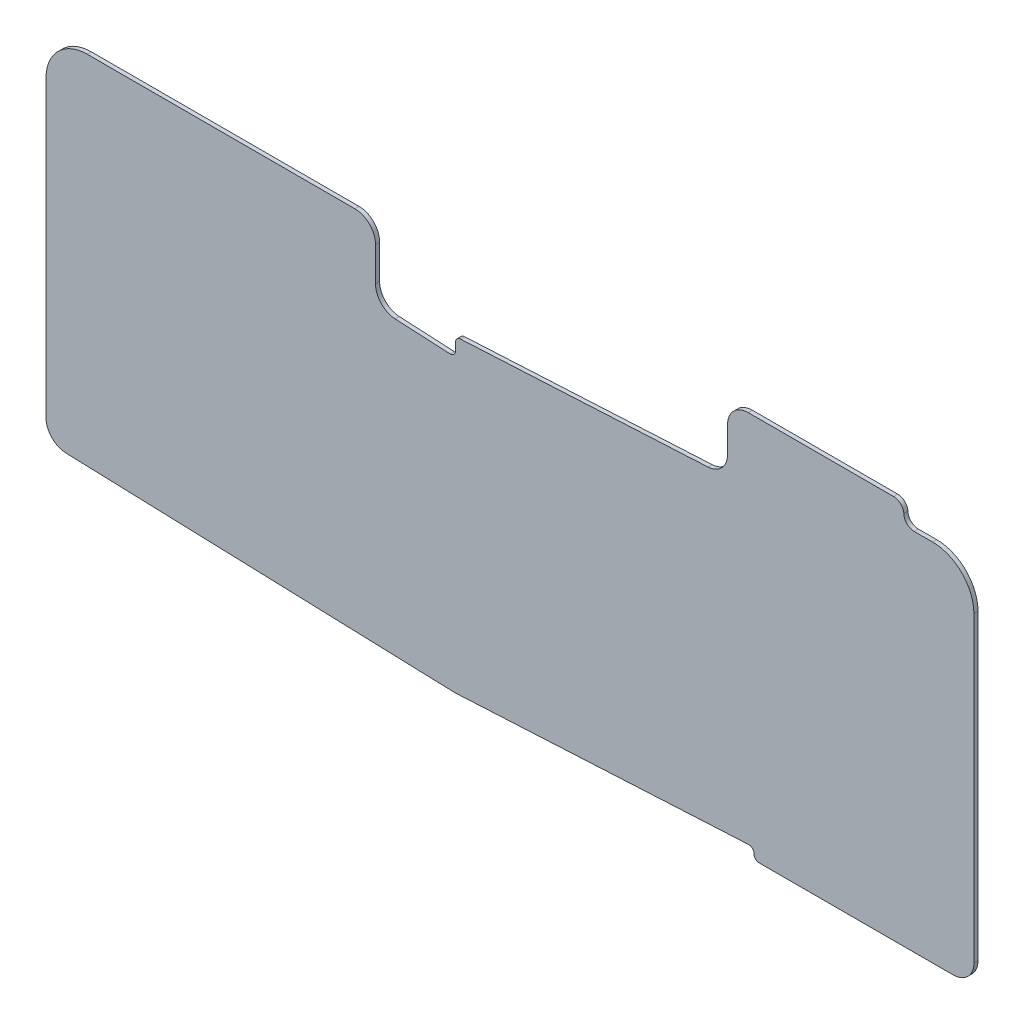
SolidWorks part; units mm, degrees
ref_plane "Piano frontale" through (0, 0, 0) normal (0, 0, 1) x (1, 0, 0)
ref_plane "Piano superiore" through (0, 0, 0) normal (0, 1, 0) x (1, 0, 0)
ref_plane "Piano destro" through (0, 0, 0) normal (1, 0, 0) x (0, 0, -1)
sketch "0" plane through (0, 0, 0) normal (0, 0, 1) x (1, 0, 0)
  line L0 (125.7508, 8.9093) -> (125.7508, 7.9088)
  line L1 (-146.1819, 97.2784) -> (-146.1819, 96.2779)
  line L2 (125.7508, 7.9088) -> (124.9498, 7.9088)
  line L3 (-146.1819, 96.2779) -> (-146.9829, 96.2779)
  line L4 (124.9498, 7.9088) -> (124.9498, 4.8082)
  line L5 (-146.9829, 96.2779) -> (-146.9829, 93.1773)
  line L6 (124.9498, 4.8082) -> (125.7508, 4.8082)
  line L7 (-146.9829, 93.1773) -> (-146.1819, 93.1773)
  line L8 (125.7508, 4.8082) -> (125.7508, -0.9905)
  line L9 (-146.1819, 93.1773) -> (-146.1819, 87.3786)
  line L10 (125.7508, -0.9905) -> (124.9498, -0.9905)
  line L11 (-146.1819, 87.3786) -> (-146.9829, 87.3786)
  line L12 (124.9498, -0.9905) -> (124.9498, -4.0911)
  line L13 (-146.9829, 87.3786) -> (-146.9829, 84.278)
  line L14 (124.9498, -4.0911) -> (125.7508, -4.0911)
  line L15 (-146.9829, 84.278) -> (-146.1819, 84.278)
  line L16 (125.7508, -4.0911) -> (125.7508, -5.0916)
  line L17 (-146.1819, 84.278) -> (-146.1819, 83.2776)
  line L18 (125.7508, -5.0916) -> (139.7498, -5.0916)
  line L19 (-146.1819, 83.2776) -> (-132.1829, 83.2776)
  line L20 (139.7498, -5.0916) -> (139.7498, -4.0911)
  line L21 (-132.1829, 83.2776) -> (-132.1829, 84.278)
  line L22 (139.7498, -4.0911) -> (140.5508, -4.0911)
  line L23 (-132.1829, 84.278) -> (-131.3819, 84.278)
  line L24 (140.5508, -4.0911) -> (140.5508, -0.9905)
  line L25 (-131.3819, 84.278) -> (-131.3819, 87.3786)
  line L26 (140.5508, -0.9905) -> (139.7498, -0.9905)
  line L27 (-131.3819, 87.3786) -> (-132.1829, 87.3786)
  line L28 (139.7498, -0.9905) -> (139.7498, 4.8082)
  line L29 (-132.1829, 87.3786) -> (-132.1829, 93.1773)
  line L30 (139.7498, 4.8082) -> (140.5508, 4.8082)
  line L31 (-132.1829, 93.1773) -> (-131.3819, 93.1773)
  line L32 (140.5508, 4.8082) -> (140.5508, 7.9088)
  line L33 (-131.3819, 93.1773) -> (-131.3819, 96.2779)
  line L34 (140.5508, 7.9088) -> (139.7498, 7.9088)
  line L35 (-131.3819, 96.2779) -> (-132.1829, 96.2779)
  line L36 (139.7498, 7.9088) -> (139.7498, 8.9093)
  line L37 (-132.1829, 96.2779) -> (-132.1829, 97.2784)
  line L38 (139.7498, 8.9093) -> (125.7508, 8.9093)
  line L39 (-132.1829, 97.2784) -> (-146.1819, 97.2784)
  line L40 (144.8008, 8.9093) -> (144.8008, 7.9088)
  line L41 (177, 32.9514) -> (177, 31.9509)
  line L42 (144.8008, 7.9088) -> (143.9998, 7.9088)
  line L43 (177, 31.9509) -> (176.199, 31.9509)
  line L44 (143.9998, 7.9088) -> (143.9998, 4.8082)
  line L45 (176.199, 31.9509) -> (176.199, 28.8503)
  line L46 (143.9998, 4.8082) -> (144.8008, 4.8082)
  line L47 (176.199, 28.8503) -> (177, 28.8503)
  line L48 (144.8008, 4.8082) -> (144.8008, -0.9905)
  line L49 (177, 28.8503) -> (177, 23.0516)
  line L50 (144.8008, -0.9905) -> (143.9998, -0.9905)
  line L51 (177, 23.0516) -> (176.199, 23.0516)
  line L52 (143.9998, -0.9905) -> (143.9998, -4.0911)
  line L53 (176.199, 23.0516) -> (176.199, 19.951)
  line L54 (143.9998, -4.0911) -> (144.8008, -4.0911)
  line L55 (176.199, 19.951) -> (177, 19.951)
  line L56 (144.8008, -4.0911) -> (144.8008, -5.0916)
  line L57 (177, 19.951) -> (177, 18.9505)
  line L58 (144.8008, -5.0916) -> (158.8008, -5.0916)
  line L59 (177, 18.9505) -> (191, 18.9505)
  line L60 (158.8008, -5.0916) -> (158.8008, -4.0911)
  line L61 (191, 18.9505) -> (191, 19.951)
  line L62 (158.8008, -4.0911) -> (159.6018, -4.0911)
  line L63 (191, 19.951) -> (191.801, 19.951)
  line L64 (159.6018, -4.0911) -> (159.6018, -0.9905)
  line L65 (191.801, 19.951) -> (191.801, 23.0516)
  line L66 (159.6018, -0.9905) -> (158.8008, -0.9905)
  line L67 (191.801, 23.0516) -> (191, 23.0516)
  line L68 (158.8008, -0.9905) -> (158.8008, 4.8082)
  line L69 (191, 23.0516) -> (191, 28.8503)
  line L70 (158.8008, 4.8082) -> (159.6018, 4.8082)
  line L71 (191, 28.8503) -> (191.801, 28.8503)
  line L72 (159.6018, 4.8082) -> (159.6018, 7.9088)
  line L73 (191.801, 28.8503) -> (191.801, 31.9509)
  line L74 (159.6018, 7.9088) -> (158.8008, 7.9088)
  line L75 (191.801, 31.9509) -> (191, 31.9509)
  line L76 (158.8008, 7.9088) -> (158.8008, 8.9093)
  line L77 (191, 31.9509) -> (191, 32.9514)
  line L78 (158.8008, 8.9093) -> (144.8008, 8.9093)
  line L79 (191, 32.9514) -> (177, 32.9514)
  line L80 (163.8488, 8.9093) -> (163.8488, 7.9088)
  line L81 (163.8488, 7.9088) -> (163.0478, 7.9088)
  line L82 (163.0478, 7.9088) -> (163.0478, 4.8082)
  line L83 (163.0478, 4.8082) -> (163.8488, 4.8082)
  line L84 (163.8488, 4.8082) -> (163.8488, -0.9905)
  line L85 (163.8488, -0.9905) -> (163.0478, -0.9905)
  line L86 (163.0478, -0.9905) -> (163.0478, -4.0911)
  line L87 (163.0478, -4.0911) -> (163.8488, -4.0911)
  line L88 (163.8488, -4.0911) -> (163.8488, -5.0916)
  line L89 (163.8488, -5.0916) -> (177.8508, -5.0916)
  line L90 (177.8508, -5.0916) -> (177.8508, -4.0911)
  line L91 (177.8508, -4.0911) -> (178.6518, -4.0911)
  line L92 (178.6518, -4.0911) -> (178.6518, -0.9905)
  line L93 (178.6518, -0.9905) -> (177.8508, -0.9905)
  line L94 (177.8508, -0.9905) -> (177.8508, 4.8082)
  line L95 (177.8508, 4.8082) -> (178.6518, 4.8082)
  line L96 (178.6518, 4.8082) -> (178.6518, 7.9088)
  line L97 (178.6518, 7.9088) -> (177.8508, 7.9088)
  line L98 (177.8508, 7.9088) -> (177.8508, 8.9093)
  line L99 (177.8508, 8.9093) -> (163.8488, 8.9093)
  line L100 (-44.1086, 8.3567) -> (-45.8316, 8.4159)
  line L101 (-45.8316, 8.4159) -> (-46.0506, 2.15)
  line L102 (-46.0506, 2.15) -> (-46.8756, 2.1789)
  line L103 (-46.8756, 2.1789) -> (-46.9726, -0.6198)
  line L104 (-46.9726, -0.6198) -> (-46.1476, -0.6488)
  line L105 (-46.1476, -0.6488) -> (-46.2616, -3.8761)
  line L106 (-46.2616, -3.8761) -> (-44.5376, -3.9367)
  line L107 (-44.5376, -3.9367) -> (-44.5686, -4.8559)
  line L108 (-44.5686, -4.8559) -> (-41.2716, -4.9717)
  line L109 (-41.2716, -4.9717) -> (-41.2396, -4.0511)
  line L110 (-41.2396, -4.0511) -> (-39.5156, -4.1118)
  line L111 (-39.5156, -4.1118) -> (-39.4026, -0.883)
  line L112 (-39.4026, -0.883) -> (-37.8786, -0.9368)
  line L113 (-37.8786, -0.9368) -> (-37.8986, -1.5362)
  line L114 (-37.8986, -1.5362) -> (-38.6986, -1.5086)
  line L115 (-38.6986, -1.5086) -> (-38.8076, -4.6065)
  line L116 (-38.8076, -4.6065) -> (-38.0066, -4.634)
  line L117 (-38.0066, -4.634) -> (-38.0426, -5.6345)
  line L118 (-38.0426, -5.6345) -> (-24.0516, -6.1223)
  line L119 (-24.0516, -6.1223) -> (-24.0156, -5.1232)
  line L120 (-24.0156, -5.1232) -> (-23.2156, -5.1522)
  line L121 (-23.2156, -5.1522) -> (-23.1086, -2.053)
  line L122 (-23.1086, -2.053) -> (-23.9076, -2.0254)
  line L123 (-23.9076, -2.0254) -> (-23.8876, -1.426)
  line L124 (-23.8876, -1.426) -> (-22.3616, -1.4783)
  line L125 (-22.3616, -1.4783) -> (-22.4746, -4.7071)
  line L126 (-22.4746, -4.7071) -> (-20.7506, -4.7677)
  line L127 (-20.7506, -4.7677) -> (-20.7826, -5.6869)
  line L128 (-20.7826, -5.6869) -> (-17.4846, -5.8012)
  line L129 (-17.4846, -5.8012) -> (-17.4526, -4.8821)
  line L130 (-17.4526, -4.8821) -> (-15.7296, -4.9427)
  line L131 (-15.7296, -4.9427) -> (-15.6176, -1.714)
  line L132 (-15.6176, -1.714) -> (-14.7916, -1.7443)
  line L133 (-14.7916, -1.7443) -> (-14.6946, 1.0558)
  line L134 (-14.6946, 1.0558) -> (-15.5186, 1.0834)
  line L135 (-15.5186, 1.0834) -> (-15.3006, 7.3507)
  line L136 (-15.3006, 7.3507) -> (-17.0246, 7.41)
  line L137 (-17.0246, 7.41) -> (-16.9906, 8.3898)
  line L138 (-16.9906, 8.3898) -> (-20.2876, 8.5041)
  line L139 (-20.2876, 8.5041) -> (-20.3226, 7.5257)
  line L140 (-20.3226, 7.5257) -> (-22.0466, 7.585)
  line L141 (-22.0466, 7.585) -> (-22.2016, 3.1188)
  line L142 (-22.2016, 3.1188) -> (-23.7266, 3.1711)
  line L143 (-23.7266, 3.1711) -> (-23.7056, 3.7719)
  line L144 (-23.7056, 3.7719) -> (-22.9056, 3.743)
  line L145 (-22.9056, 3.743) -> (-22.7976, 6.8409)
  line L146 (-22.7976, 6.8409) -> (-23.5966, 6.8698)
  line L147 (-23.5966, 6.8698) -> (-23.5626, 7.8688)
  line L148 (-23.5626, 7.8688) -> (-37.5536, 8.3567)
  line L149 (-37.5536, 8.3567) -> (-37.5876, 7.3576)
  line L150 (-37.5876, 7.3576) -> (-38.3886, 7.3852)
  line L151 (-38.3886, 7.3852) -> (-38.4956, 4.2873)
  line L152 (-38.4956, 4.2873) -> (-37.6966, 4.2598)
  line L153 (-37.6966, 4.2598) -> (-37.7186, 3.6603)
  line L154 (-37.7186, 3.6603) -> (-39.2426, 3.7127)
  line L155 (-39.2426, 3.7127) -> (-39.0856, 8.1803)
  line L156 (23.7194, 8.1189) -> (23.7717, 7.1212)
  line L157 (-39.0856, 8.1803) -> (-40.8096, 8.2409)
  line L158 (23.7717, 7.1212) -> (22.9718, 7.0792)
  line L159 (-40.8096, 8.2409) -> (-40.7756, 9.2207)
  line L160 (22.9718, 7.0792) -> (23.1341, 3.9829)
  line L161 (-40.7756, 9.2207) -> (-44.0726, 9.3351)
  line L162 (23.1341, 3.9829) -> (23.934, 4.0248)
  line L163 (-44.0726, 9.3351) -> (-44.1086, 8.3567)
  line L164 (23.934, 4.0248) -> (23.9653, 3.4262)
  line L165 (23.9653, 3.4262) -> (22.4414, 3.3464)
  line L166 (22.4414, 3.3464) -> (22.2724, 6.572)
  line L167 (22.2724, 6.572) -> (20.5498, 6.4818)
  line L168 (20.5498, 6.4818) -> (20.5017, 7.3996)
  line L169 (20.5017, 7.3996) -> (17.2072, 7.2269)
  line L170 (17.2072, 7.2269) -> (17.2553, 6.3091)
  line L171 (17.2553, 6.3091) -> (15.5326, 6.2188)
  line L172 (15.5326, 6.2188) -> (15.7017, 2.9931)
  line L173 (15.7017, 2.9931) -> (14.8768, 2.9499)
  line L174 (14.8768, 2.9499) -> (15.0234, 0.1536)
  line L175 (15.0234, 0.1536) -> (15.8482, 0.1968)
  line L176 (15.8482, 0.1968) -> (16.1764, -6.0647)
  line L177 (16.1764, -6.0647) -> (17.899, -5.9744)
  line L178 (17.899, -5.9744) -> (17.9503, -6.9529)
  line L179 (17.9503, -6.9529) -> (21.2448, -6.7802)
  line L180 (21.2448, -6.7802) -> (21.1935, -5.8018)
  line L181 (21.1935, -5.8018) -> (22.9161, -5.7115)
  line L182 (22.9161, -5.7115) -> (22.6822, -1.2472)
  line L183 (22.6822, -1.2472) -> (24.2061, -1.1674)
  line L184 (24.2061, -1.1674) -> (24.2375, -1.7674)
  line L185 (24.2375, -1.7674) -> (23.4376, -1.8094)
  line L186 (23.4376, -1.8094) -> (23.5998, -4.9043)
  line L187 (23.5998, -4.9043) -> (24.3997, -4.8624)
  line L188 (24.3997, -4.8624) -> (24.4521, -5.8614)
  line L189 (24.4521, -5.8614) -> (38.4319, -5.1288)
  line L190 (38.4319, -5.1288) -> (38.3796, -4.1297)
  line L191 (38.3796, -4.1297) -> (39.1795, -4.0878)
  line L192 (39.1795, -4.0878) -> (39.0173, -0.9929)
  line L193 (39.0173, -0.9929) -> (38.2174, -1.0348)
  line L194 (38.2174, -1.0348) -> (38.1859, -0.4347)
  line L195 (38.1859, -0.4347) -> (39.7098, -0.3549)
  line L196 (39.7098, -0.3549) -> (39.9438, -4.8191)
  line L197 (39.9438, -4.8191) -> (41.6664, -4.7288)
  line L198 (41.6664, -4.7288) -> (41.7177, -5.7073)
  line L199 (41.7177, -5.7073) -> (45.0122, -5.5346)
  line L200 (45.0122, -5.5346) -> (44.9609, -4.5562)
  line L201 (44.9609, -4.5562) -> (46.6835, -4.4659)
  line L202 (46.6835, -4.4659) -> (46.3554, 1.7956)
  line L203 (46.3554, 1.7956) -> (47.1802, 1.8388)
  line L204 (47.1802, 1.8388) -> (47.0337, 4.6352)
  line L205 (47.0337, 4.6352) -> (46.2088, 4.592)
  line L206 (46.2088, 4.592) -> (46.0398, 7.8176)
  line L207 (46.0398, 7.8176) -> (44.3171, 7.7274)
  line L208 (44.3171, 7.7274) -> (44.269, 8.6452)
  line L209 (44.269, 8.6452) -> (40.9746, 8.4725)
  line L210 (40.9746, 8.4725) -> (41.0227, 7.5547)
  line L211 (41.0227, 7.5547) -> (39.3, 7.4644)
  line L212 (39.3, 7.4644) -> (39.4691, 4.2387)
  line L213 (39.4691, 4.2387) -> (37.9452, 4.1589)
  line L214 (37.9452, 4.1589) -> (37.9138, 4.7575)
  line L215 (37.9138, 4.7575) -> (38.7137, 4.7994)
  line L216 (38.7137, 4.7994) -> (38.5514, 7.8957)
  line L217 (38.5514, 7.8957) -> (37.7515, 7.8538)
  line L218 (37.7515, 7.8538) -> (37.6992, 8.8515)
  line L219 (37.6992, 8.8515) -> (23.7194, 8.1189)
  line L220 (-124.5132, 10.6803) -> (-124.5132, 9.6812)
  line L221 (-124.5132, 9.6812) -> (-125.3122, 9.6812)
  line L222 (-125.3122, 9.6812) -> (-125.3122, 6.5806)
  line L223 (-125.3122, 6.5806) -> (-124.5132, 6.5806)
  line L224 (-124.5132, 6.5806) -> (-124.5132, 0.7804)
  line L225 (-124.5132, 0.7804) -> (-125.3122, 0.7804)
  line L226 (-125.3122, 0.7804) -> (-125.3122, -2.3188)
  line L227 (-125.3122, -2.3188) -> (-124.5132, -2.3188)
  line L228 (-124.5132, -2.3188) -> (-124.5132, -3.3192)
  line L229 (-124.5132, -3.3192) -> (-110.5121, -3.3192)
  line L230 (-110.5121, -3.3192) -> (-110.5121, -2.3188)
  line L231 (-110.5121, -2.3188) -> (-109.7127, -2.3188)
  line L232 (-109.7127, -2.3188) -> (-109.7127, 0.7804)
  line L233 (-109.7127, 0.7804) -> (-110.5121, 0.7804)
  line L234 (-110.5121, 0.7804) -> (-110.5121, 6.5806)
  line L235 (-110.5121, 6.5806) -> (-109.7127, 6.5806)
  line L236 (-109.7127, 6.5806) -> (-109.7127, 9.6812)
  line L237 (-109.7127, 9.6812) -> (-110.5121, 9.6812)
  line L238 (-110.5121, 9.6812) -> (-110.5121, 10.6803)
  line L239 (-110.5121, 10.6803) -> (-124.5132, 10.6803)
  line L240 (-99.5931, 10.2215) -> (-99.628, 9.223)
  line L241 (-99.628, 9.223) -> (-100.4275, 9.2509)
  line L242 (-100.4275, 9.2509) -> (-100.5357, 6.1522)
  line L243 (-100.5357, 6.1522) -> (-99.7362, 6.1243)
  line L244 (-99.7362, 6.1243) -> (-99.9386, 0.3276)
  line L245 (-99.9386, 0.3276) -> (-100.7381, 0.3556)
  line L246 (-100.7381, 0.3556) -> (-100.8463, -2.7417)
  line L247 (-100.8463, -2.7417) -> (-100.0468, -2.7697)
  line L248 (-100.0468, -2.7697) -> (-100.0817, -3.7695)
  line L249 (-100.0817, -3.7695) -> (-86.0902, -4.258)
  line L250 (-86.0902, -4.258) -> (-86.0553, -3.2583)
  line L251 (-86.0553, -3.2583) -> (-85.2548, -3.2862)
  line L252 (-85.2548, -3.2862) -> (-85.1466, -0.1889)
  line L253 (-85.1466, -0.1889) -> (-85.9471, -0.1609)
  line L254 (-85.9471, -0.1609) -> (-85.7447, 5.6357)
  line L255 (-85.7447, 5.6357) -> (-84.9442, 5.6078)
  line L256 (-84.9442, 5.6078) -> (-84.836, 8.7065)
  line L257 (-84.836, 8.7065) -> (-85.6365, 8.7344)
  line L258 (-85.6365, 8.7344) -> (-85.6016, 9.7329)
  line L259 (-85.6016, 9.7329) -> (-99.5931, 10.2215)
  line L260 (-74.7946, 9.3905) -> (-74.8295, 8.392)
  line L261 (-74.8295, 8.392) -> (-75.628, 8.4198)
  line L262 (-75.628, 8.4198) -> (-75.7362, 5.3211)
  line L263 (-75.7362, 5.3211) -> (-74.9377, 5.2933)
  line L264 (-74.9377, 5.2933) -> (-75.1401, -0.5034)
  line L265 (-75.1401, -0.5034) -> (-75.9386, -0.4755)
  line L266 (-75.9386, -0.4755) -> (-76.0468, -3.5728)
  line L267 (-76.0468, -3.5728) -> (-75.2483, -3.6007)
  line L268 (-75.2483, -3.6007) -> (-75.2832, -4.6005)
  line L269 (-75.2832, -4.6005) -> (-61.2907, -5.0891)
  line L270 (-61.2907, -5.0891) -> (-61.2558, -4.0894)
  line L271 (-61.2558, -4.0894) -> (-60.4573, -4.1172)
  line L272 (-60.4573, -4.1172) -> (-60.3491, -1.0199)
  line L273 (-60.3491, -1.0199) -> (-61.1476, -0.992)
  line L274 (-61.1476, -0.992) -> (-60.9452, 4.8046)
  line L275 (-60.9452, 4.8046) -> (-60.1467, 4.7767)
  line L276 (-60.1467, 4.7767) -> (-60.0385, 7.8755)
  line L277 (-60.0385, 7.8755) -> (-60.837, 7.9033)
  line L278 (-60.837, 7.9033) -> (-60.8021, 8.9018)
  line L279 (-60.8021, 8.9018) -> (-74.7946, 9.3905)
  line L280 (61.1769, 9.8704) -> (61.2292, 8.8726)
  line L281 (61.2292, 8.8726) -> (60.4293, 8.8307)
  line L282 (60.4293, 8.8307) -> (60.5915, 5.7344)
  line L283 (60.5915, 5.7344) -> (61.3914, 5.7763)
  line L284 (61.3914, 5.7763) -> (61.695, -0.016)
  line L285 (61.695, -0.016) -> (60.8951, -0.0579)
  line L286 (60.8951, -0.0579) -> (61.0573, -3.1528)
  line L287 (61.0573, -3.1528) -> (61.8572, -3.1109)
  line L288 (61.8572, -3.1109) -> (61.9096, -4.1099)
  line L289 (61.9096, -4.1099) -> (75.8894, -3.3773)
  line L290 (75.8894, -3.3773) -> (75.837, -2.3783)
  line L291 (75.837, -2.3783) -> (76.6369, -2.3363)
  line L292 (76.6369, -2.3363) -> (76.4747, 0.7586)
  line L293 (76.4747, 0.7586) -> (75.6748, 0.7167)
  line L294 (75.6748, 0.7167) -> (75.3713, 6.5089)
  line L295 (75.3713, 6.5089) -> (76.1712, 6.5509)
  line L296 (76.1712, 6.5509) -> (76.0089, 9.6472)
  line L297 (76.0089, 9.6472) -> (75.209, 9.6053)
  line L298 (75.209, 9.6053) -> (75.1567, 10.603)
  line L299 (75.1567, 10.603) -> (61.1769, 9.8704)
  line L300 (84.9562, 11.1166) -> (85.0085, 10.1189)
  line L301 (85.0085, 10.1189) -> (84.2106, 10.077)
  line L302 (84.2106, 10.077) -> (84.3729, 6.9807)
  line L303 (84.3729, 6.9807) -> (85.1708, 7.0225)
  line L304 (85.1708, 7.0225) -> (85.4744, 1.2303)
  line L305 (85.4744, 1.2303) -> (84.6765, 1.1884)
  line L306 (84.6765, 1.1884) -> (84.8387, -1.9065)
  line L307 (84.8387, -1.9065) -> (85.6366, -1.8647)
  line L308 (85.6366, -1.8647) -> (85.6889, -2.8637)
  line L309 (85.6889, -2.8637) -> (99.6697, -2.131)
  line L310 (99.6697, -2.131) -> (99.6174, -1.132)
  line L311 (99.6174, -1.132) -> (100.4163, -1.0901)
  line L312 (100.4163, -1.0901) -> (100.2541, 2.0048)
  line L313 (100.2541, 2.0048) -> (99.4552, 1.963)
  line L314 (99.4552, 1.963) -> (99.1516, 7.7552)
  line L315 (99.1516, 7.7552) -> (99.9505, 7.7971)
  line L316 (99.9505, 7.7971) -> (99.7882, 10.8934)
  line L317 (99.7882, 10.8934) -> (98.9893, 10.8516)
  line L318 (98.9893, 10.8516) -> (98.9371, 11.8493)
  line L319 (98.9371, 11.8493) -> (84.9562, 11.1166)
  line L320 (144.8008, 27.9592) -> (144.8008, 26.9588)
  line L321 (177, 52.0013) -> (177, 51.0009)
  line L322 (177, 71.0513) -> (177, 70.0509)
  line L323 (144.8008, 26.9588) -> (143.9998, 26.9588)
  line L324 (177, 51.0009) -> (176.199, 51.0009)
  line L325 (177, 70.0509) -> (176.199, 70.0509)
  line L326 (143.9998, 26.9588) -> (143.9998, 23.8582)
  line L327 (176.199, 51.0009) -> (176.199, 47.9003)
  line L328 (176.199, 70.0509) -> (176.199, 66.9503)
  line L329 (143.9998, 23.8582) -> (144.8008, 23.8582)
  line L330 (176.199, 47.9003) -> (177, 47.9003)
  line L331 (176.199, 66.9503) -> (177, 66.9503)
  line L332 (144.8008, 23.8582) -> (144.8008, 18.0595)
  line L333 (177, 47.9003) -> (177, 42.1016)
  line L334 (177, 66.9503) -> (177, 61.1516)
  line L335 (144.8008, 18.0595) -> (143.9998, 18.0595)
  line L336 (177, 42.1016) -> (176.199, 42.1016)
  line L337 (177, 61.1516) -> (176.199, 61.1516)
  line L338 (143.9998, 18.0595) -> (143.9998, 14.9589)
  line L339 (176.199, 42.1016) -> (176.199, 39.001)
  line L340 (176.199, 61.1516) -> (176.199, 58.051)
  line L341 (143.9998, 14.9589) -> (144.8008, 14.9589)
  line L342 (176.199, 39.001) -> (177, 39.001)
  line L343 (176.199, 58.051) -> (177, 58.051)
  line L344 (144.8008, 14.9589) -> (144.8008, 13.9584)
  line L345 (177, 39.001) -> (177, 38.0005)
  line L346 (177, 58.051) -> (177, 57.0505)
  line L347 (144.8008, 13.9584) -> (158.8008, 13.9584)
  line L348 (177, 38.0005) -> (191, 38.0005)
  line L349 (177, 57.0505) -> (191, 57.0505)
  line L350 (158.8008, 13.9584) -> (158.8008, 14.9589)
  line L351 (191, 38.0005) -> (191, 39.001)
  line L352 (191, 57.0505) -> (191, 58.051)
  line L353 (158.8008, 14.9589) -> (159.6018, 14.9589)
  line L354 (191, 39.001) -> (191.801, 39.001)
  line L355 (191, 58.051) -> (191.801, 58.051)
  line L356 (159.6018, 14.9589) -> (159.6018, 18.0595)
  line L357 (191.801, 39.001) -> (191.801, 42.1016)
  line L358 (191.801, 58.051) -> (191.801, 61.1516)
  line L359 (159.6018, 18.0595) -> (158.8008, 18.0595)
  line L360 (191.801, 42.1016) -> (191, 42.1016)
  line L361 (191.801, 61.1516) -> (191, 61.1516)
  line L362 (158.8008, 18.0595) -> (158.8008, 23.8582)
  line L363 (191, 42.1016) -> (191, 47.9003)
  line L364 (191, 61.1516) -> (191, 66.9503)
  line L365 (158.8008, 23.8582) -> (159.6018, 23.8582)
  line L366 (191, 47.9003) -> (191.801, 47.9003)
  line L367 (191, 66.9503) -> (191.801, 66.9503)
  line L368 (159.6018, 23.8582) -> (159.6018, 26.9588)
  line L369 (191.801, 47.9003) -> (191.801, 51.0009)
  line L370 (191.801, 66.9503) -> (191.801, 70.0509)
  line L371 (159.6018, 26.9588) -> (158.8008, 26.9588)
  line L372 (191.801, 51.0009) -> (191, 51.0009)
  line L373 (191.801, 70.0509) -> (191, 70.0509)
  line L374 (158.8008, 26.9588) -> (158.8008, 27.9592)
  line L375 (191, 51.0009) -> (191, 52.0013)
  line L376 (191, 70.0509) -> (191, 71.0513)
  line L377 (158.8008, 27.9592) -> (144.8008, 27.9592)
  line L378 (191, 52.0013) -> (177, 52.0013)
  line L379 (191, 71.0513) -> (177, 71.0513)
  line L380 (27, 88.0936) -> (-28, 88.0936)
  line L381 (-7, 7) -> (-7, 6.0009)
  line L382 (-148.7544, 21.6507) -> (-149.5548, 21.6507)
  line L383 (-7, 6.0009) -> (-7.8004, 6.0009)
  line L384 (-149.5548, 21.6507) -> (-149.5548, 18.5501)
  line L385 (-7.8004, 6.0009) -> (-7.8004, 2.9003)
  line L386 (-149.5548, 18.5501) -> (-148.7544, 18.5501)
  line L387 (-7.8004, 2.9003) -> (-7, 2.9003)
  line L388 (-106.1319, 84.277) -> (-161, 84.277)
  line L389 (-7, 2.9003) -> (-7, -2.8999)
  line L390 (-148.7544, 12.7499) -> (-149.5548, 12.7499)
  line L391 (-7, -2.8999) -> (-7.8004, -2.8999)
  line L392 (-149.5548, 12.7499) -> (-149.5548, 9.6507)
  line L393 (-7.8004, -2.8999) -> (-7.8004, -5.9991)
  line L394 (-149.5548, 9.6507) -> (-148.7544, 9.6507)
  line L395 (-7.8004, -5.9991) -> (-7, -5.9991)
  line L397 (-7, -5.9991) -> (-7, -6.9995)
  line L398 (-148.7544, 8.6503) -> (-134.7547, 8.6503)
  line L399 (-7, -6.9995) -> (6.9997, -6.9995)
  line L400 (-134.7547, 8.6503) -> (-134.7547, 9.6507)
  line L401 (6.9997, -6.9995) -> (6.9997, -5.9991)
  line L402 (-134.7547, 9.6507) -> (-133.9557, 9.6507)
  line L403 (6.9997, -5.9991) -> (7.7987, -5.9991)
  line L404 (-133.9557, 9.6507) -> (-133.9557, 12.7499)
  line L405 (7.7987, -5.9991) -> (7.7987, -2.8999)
  line L406 (-133.9557, 12.7499) -> (-134.7547, 12.7499)
  line L407 (7.7987, -2.8999) -> (6.9997, -2.8999)
  line L408 (-134.7547, 12.7499) -> (-134.7547, 18.5501)
  line L409 (6.9997, -2.8999) -> (6.9997, 2.9003)
  line L410 (-134.7547, 18.5501) -> (-133.9557, 18.5501)
  line L411 (6.9997, 2.9003) -> (7.7987, 2.9003)
  line L412 (-133.9557, 18.5501) -> (-133.9557, 21.6507)
  line L413 (7.7987, 2.9003) -> (7.7987, 6.0009)
  line L414 (-133.9557, 21.6507) -> (-134.7547, 21.6507)
  line L415 (7.7987, 6.0009) -> (6.9997, 6.0009)
  line L416 (-134.7547, 21.6507) -> (-134.7547, 22.6498)
  line L417 (6.9997, 6.0009) -> (6.9997, 7)
  line L418 (-134.7547, 22.6498) -> (-148.7544, 22.6498)
  line L419 (6.9997, 7) -> (-7, 7)
  line L420 (-124.5132, 34.1285) -> (-124.5132, 33.128)
  line L421 (-124.5132, 33.128) -> (-125.3122, 33.128)
  line L422 (-125.3122, 33.128) -> (-125.3122, 30.0285)
  line L423 (-125.3122, 30.0285) -> (-124.5132, 30.0285)
  line L424 (-124.5132, 30.0285) -> (-124.5132, 24.2271)
  line L425 (-124.5132, 24.2271) -> (-125.3122, 24.2271)
  line L426 (-125.3122, 24.2271) -> (-125.3122, 21.1279)
  line L427 (-125.3122, 21.1279) -> (-124.5132, 21.1279)
  line L428 (-124.5132, 21.1279) -> (-124.5132, 20.1275)
  line L429 (-124.5132, 20.1275) -> (-110.5121, 20.1275)
  line L430 (-110.5121, 20.1275) -> (-110.5121, 21.1279)
  line L431 (-110.5121, 21.1279) -> (-109.7127, 21.1279)
  line L432 (-109.7127, 21.1279) -> (-109.7127, 24.2271)
  line L433 (-109.7127, 24.2271) -> (-110.5121, 24.2271)
  line L434 (-110.5121, 24.2271) -> (-110.5121, 30.0285)
  line L435 (-110.5121, 30.0285) -> (-109.7127, 30.0285)
  line L436 (-109.7127, 30.0285) -> (-109.7127, 33.128)
  line L437 (-109.7127, 33.128) -> (-110.5121, 33.128)
  line L438 (-110.5121, 33.128) -> (-110.5121, 34.1285)
  line L439 (-110.5121, 34.1285) -> (-124.5132, 34.1285)
  line L440 (-101.1692, 33.8521) -> (-101.2216, 32.853)
  line L441 (-101.2216, 32.853) -> (-102.0194, 32.8948)
  line L442 (-102.0194, 32.8948) -> (-102.1816, 29.7996)
  line L443 (-102.1816, 29.7996) -> (-101.3838, 29.7578)
  line L444 (-101.3838, 29.7578) -> (-101.6874, 23.9643)
  line L445 (-101.6874, 23.9643) -> (-102.4852, 24.0061)
  line L446 (-102.4852, 24.0061) -> (-102.6474, 20.9112)
  line L447 (-102.6474, 20.9112) -> (-101.8496, 20.8694)
  line L448 (-101.8496, 20.8694) -> (-101.902, 19.8703)
  line L449 (-101.902, 19.8703) -> (-87.9211, 19.1376)
  line L450 (-87.9211, 19.1376) -> (-87.8688, 20.1367)
  line L451 (-87.8688, 20.1367) -> (-87.0689, 20.0947)
  line L452 (-87.0689, 20.0947) -> (-86.9067, 23.1897)
  line L453 (-86.9067, 23.1897) -> (-87.7066, 23.2316)
  line L454 (-87.7066, 23.2316) -> (-87.403, 29.0251)
  line L455 (-87.403, 29.0251) -> (-86.6031, 28.9831)
  line L456 (-86.6031, 28.9831) -> (-86.4409, 32.0784)
  line L457 (-86.4409, 32.0784) -> (-87.2408, 32.1203)
  line L458 (-87.2408, 32.1203) -> (-87.1884, 33.1194)
  line L459 (-87.1884, 33.1194) -> (-101.1692, 33.8521)
  line L460 (-82.1453, 32.8551) -> (-82.1977, 31.856)
  line L461 (-82.1977, 31.856) -> (-82.9956, 31.8978)
  line L462 (-82.9956, 31.8978) -> (-83.1578, 28.8026)
  line L463 (-83.1578, 28.8026) -> (-82.3599, 28.7608)
  line L464 (-82.3599, 28.7608) -> (-82.6635, 22.9673)
  line L465 (-82.6635, 22.9673) -> (-83.4614, 23.0091)
  line L466 (-83.4614, 23.0091) -> (-83.6236, 19.9142)
  line L467 (-83.6236, 19.9142) -> (-82.8257, 19.8724)
  line L468 (-82.8257, 19.8724) -> (-82.8781, 18.8733)
  line L469 (-82.8781, 18.8733) -> (-68.8973, 18.1406)
  line L470 (-68.8973, 18.1406) -> (-68.8449, 19.1397)
  line L471 (-68.8449, 19.1397) -> (-68.045, 19.0977)
  line L472 (-68.045, 19.0977) -> (-67.8828, 22.1927)
  line L473 (-67.8828, 22.1927) -> (-68.6827, 22.2346)
  line L474 (-68.6827, 22.2346) -> (-68.3791, 28.0281)
  line L475 (-68.3791, 28.0281) -> (-67.5792, 27.9861)
  line L476 (-67.5792, 27.9861) -> (-67.417, 31.0814)
  line L477 (-67.417, 31.0814) -> (-68.2169, 31.1233)
  line L478 (-68.2169, 31.1233) -> (-68.1645, 32.1224)
  line L479 (-68.1645, 32.1224) -> (-82.1453, 32.8551)
  line L480 (-63.1214, 31.8581) -> (-63.1738, 30.859)
  line L481 (-63.1738, 30.859) -> (-63.9717, 30.9008)
  line L482 (-63.9717, 30.9008) -> (-64.1339, 27.8056)
  line L483 (-64.1339, 27.8056) -> (-63.336, 27.7638)
  line L484 (-63.336, 27.7638) -> (-63.6396, 21.9703)
  line L485 (-63.6396, 21.9703) -> (-64.4375, 22.0121)
  line L486 (-64.4375, 22.0121) -> (-64.5997, 18.9172)
  line L487 (-64.5997, 18.9172) -> (-63.8018, 18.8754)
  line L488 (-63.8018, 18.8754) -> (-63.8542, 17.8763)
  line L489 (-63.8542, 17.8763) -> (-49.8734, 17.1436)
  line L490 (-49.8734, 17.1436) -> (-49.821, 18.1427)
  line L491 (-49.821, 18.1427) -> (-49.0211, 18.1007)
  line L492 (-49.0211, 18.1007) -> (-48.8589, 21.1957)
  line L493 (-48.8589, 21.1957) -> (-49.6588, 21.2376)
  line L494 (-49.6588, 21.2376) -> (-49.3552, 27.0311)
  line L495 (-49.3552, 27.0311) -> (-48.5553, 26.9891)
  line L496 (-48.5553, 26.9891) -> (-48.3931, 30.0844)
  line L497 (-48.3931, 30.0844) -> (-49.193, 30.1263)
  line L498 (-49.193, 30.1263) -> (-49.1406, 31.1254)
  line L499 (-49.1406, 31.1254) -> (-63.1214, 31.8581)
  line L500 (-44.0975, 30.8611) -> (-44.1499, 29.862)
  line L501 (-44.1499, 29.862) -> (-44.9478, 29.9038)
  line L502 (-44.9478, 29.9038) -> (-45.11, 26.8086)
  line L503 (-45.11, 26.8086) -> (-44.3121, 26.7668)
  line L504 (-44.3121, 26.7668) -> (-44.6157, 20.9733)
  line L505 (-44.6157, 20.9733) -> (-45.4136, 21.0151)
  line L506 (-45.4136, 21.0151) -> (-45.5758, 17.9202)
  line L507 (-45.5758, 17.9202) -> (-44.7779, 17.8784)
  line L508 (-44.7779, 17.8784) -> (-44.8303, 16.8793)
  line L509 (-44.8303, 16.8793) -> (-30.8495, 16.1466)
  line L510 (-30.8495, 16.1466) -> (-30.7971, 17.1457)
  line L511 (-30.7971, 17.1457) -> (-29.9972, 17.1037)
  line L512 (-29.9972, 17.1037) -> (-29.835, 20.1987)
  line L513 (-29.835, 20.1987) -> (-30.6349, 20.2406)
  line L514 (-30.6349, 20.2406) -> (-30.3313, 26.0341)
  line L515 (-30.3313, 26.0341) -> (-29.5314, 25.9921)
  line L516 (-29.5314, 25.9921) -> (-29.3692, 29.0874)
  line L517 (-29.3692, 29.0874) -> (-30.1691, 29.1293)
  line L518 (-30.1691, 29.1293) -> (-30.1167, 30.1284)
  line L519 (-30.1167, 30.1284) -> (-44.0975, 30.8611)
  line L520 (-25.0736, 29.8641) -> (-25.126, 28.865)
  line L521 (-25.126, 28.865) -> (-25.9239, 28.9068)
  line L522 (-25.9239, 28.9068) -> (-26.0861, 25.8116)
  line L523 (-26.0861, 25.8116) -> (-25.2882, 25.7698)
  line L524 (-25.2882, 25.7698) -> (-25.5918, 19.9763)
  line L525 (-25.5918, 19.9763) -> (-26.3897, 20.0181)
  line L526 (-26.3897, 20.0181) -> (-26.5519, 16.9232)
  line L527 (-26.5519, 16.9232) -> (-25.754, 16.8814)
  line L528 (-25.754, 16.8814) -> (-25.8064, 15.8823)
  line L529 (-25.8064, 15.8823) -> (-11.8256, 15.1496)
  line L530 (-11.8256, 15.1496) -> (-11.7732, 16.1487)
  line L531 (-11.7732, 16.1487) -> (-10.9733, 16.1067)
  line L532 (-10.9733, 16.1067) -> (-10.8111, 19.2017)
  line L533 (-10.8111, 19.2017) -> (-11.611, 19.2436)
  line L534 (-11.611, 19.2436) -> (-11.3074, 25.0371)
  line L535 (-11.3074, 25.0371) -> (-10.5075, 24.9951)
  line L536 (-10.5075, 24.9951) -> (-10.3453, 28.0904)
  line L537 (-10.3453, 28.0904) -> (-11.1452, 28.1323)
  line L538 (-11.1452, 28.1323) -> (-11.0928, 29.1314)
  line L539 (-11.0928, 29.1314) -> (-25.0736, 29.8641)
  line L540 (11.0928, 29.1314) -> (11.1452, 28.1323)
  line L541 (11.1452, 28.1323) -> (10.3453, 28.0904)
  line L542 (10.3453, 28.0904) -> (10.5075, 24.9951)
  line L543 (10.5075, 24.9951) -> (11.3074, 25.0371)
  line L544 (11.3074, 25.0371) -> (11.611, 19.2436)
  line L545 (11.611, 19.2436) -> (10.8111, 19.2017)
  line L546 (10.8111, 19.2017) -> (10.9733, 16.1067)
  line L547 (10.9733, 16.1067) -> (11.7732, 16.1487)
  line L548 (11.7732, 16.1487) -> (11.8256, 15.1496)
  line L549 (11.8256, 15.1496) -> (25.8054, 15.8823)
  line L550 (25.8054, 15.8823) -> (25.753, 16.8813)
  line L551 (25.753, 16.8813) -> (26.5529, 16.9232)
  line L552 (26.5529, 16.9232) -> (26.3907, 20.0182)
  line L553 (26.3907, 20.0182) -> (25.5908, 19.9763)
  line L554 (25.5908, 19.9763) -> (25.2872, 25.7697)
  line L555 (25.2872, 25.7697) -> (26.0871, 25.8116)
  line L556 (26.0871, 25.8116) -> (25.9249, 28.9069)
  line L557 (25.9249, 28.9069) -> (25.125, 28.865)
  line L558 (25.125, 28.865) -> (25.0726, 29.8641)
  line L559 (25.0726, 29.8641) -> (11.0928, 29.1314)
  line L560 (30.1167, 30.1284) -> (30.1691, 29.1293)
  line L561 (30.1691, 29.1293) -> (29.3692, 29.0874)
  line L562 (29.3692, 29.0874) -> (29.5314, 25.9921)
  line L563 (29.5314, 25.9921) -> (30.3313, 26.0341)
  line L564 (30.3313, 26.0341) -> (30.6349, 20.2406)
  line L565 (30.6349, 20.2406) -> (29.835, 20.1987)
  line L566 (29.835, 20.1987) -> (29.9972, 17.1037)
  line L567 (29.9972, 17.1037) -> (30.7971, 17.1457)
  line L568 (30.7971, 17.1457) -> (30.8495, 16.1466)
  line L569 (30.8495, 16.1466) -> (44.8293, 16.8793)
  line L570 (44.8293, 16.8793) -> (44.7769, 17.8783)
  line L571 (44.7769, 17.8783) -> (45.5768, 17.9202)
  line L572 (45.5768, 17.9202) -> (45.4146, 21.0152)
  line L573 (45.4146, 21.0152) -> (44.6147, 20.9733)
  line L574 (44.6147, 20.9733) -> (44.3111, 26.7667)
  line L575 (44.3111, 26.7667) -> (45.111, 26.8086)
  line L576 (45.111, 26.8086) -> (44.9488, 29.9039)
  line L577 (44.9488, 29.9039) -> (44.1489, 29.862)
  line L578 (44.1489, 29.862) -> (44.0965, 30.8611)
  line L579 (44.0965, 30.8611) -> (30.1167, 30.1284)
  line L580 (49.1406, 31.1254) -> (49.193, 30.1263)
  line L581 (49.193, 30.1263) -> (48.3931, 30.0844)
  line L582 (48.3931, 30.0844) -> (48.5553, 26.9891)
  line L583 (48.5553, 26.9891) -> (49.3552, 27.0311)
  line L584 (49.3552, 27.0311) -> (49.6588, 21.2376)
  line L585 (49.6588, 21.2376) -> (48.8589, 21.1957)
  line L586 (48.8589, 21.1957) -> (49.0211, 18.1007)
  line L587 (49.0211, 18.1007) -> (49.821, 18.1427)
  line L588 (49.821, 18.1427) -> (49.8734, 17.1436)
  line L589 (49.8734, 17.1436) -> (63.8532, 17.8763)
  line L590 (63.8532, 17.8763) -> (63.8008, 18.8753)
  line L591 (63.8008, 18.8753) -> (64.5987, 18.9171)
  line L592 (64.5987, 18.9171) -> (64.4365, 22.0121)
  line L593 (64.4365, 22.0121) -> (63.6386, 21.9703)
  line L594 (63.6386, 21.9703) -> (63.335, 27.7637)
  line L595 (63.335, 27.7637) -> (64.1329, 27.8055)
  line L596 (64.1329, 27.8055) -> (63.9707, 30.9008)
  line L597 (63.9707, 30.9008) -> (63.1728, 30.859)
  line L598 (63.1728, 30.859) -> (63.1204, 31.8581)
  line L599 (63.1204, 31.8581) -> (49.1406, 31.1254)
  line L600 (68.1625, 32.1223) -> (68.2149, 31.1232)
  line L601 (68.2149, 31.1232) -> (67.417, 31.0814)
  line L602 (67.417, 31.0814) -> (67.5792, 27.9861)
  line L603 (67.5792, 27.9861) -> (68.3771, 28.0279)
  line L604 (68.3771, 28.0279) -> (68.6807, 22.2345)
  line L605 (68.6807, 22.2345) -> (67.8828, 22.1927)
  line L606 (67.8828, 22.1927) -> (68.045, 19.0977)
  line L607 (68.045, 19.0977) -> (68.8429, 19.1395)
  line L608 (68.8429, 19.1395) -> (68.8953, 18.1405)
  line L609 (68.8953, 18.1405) -> (82.8771, 18.8733)
  line L610 (82.8771, 18.8733) -> (82.8247, 19.8723)
  line L611 (82.8247, 19.8723) -> (83.6246, 19.9142)
  line L612 (83.6246, 19.9142) -> (83.4624, 23.0092)
  line L613 (83.4624, 23.0092) -> (82.6625, 22.9673)
  line L614 (82.6625, 22.9673) -> (82.3589, 28.7607)
  line L615 (82.3589, 28.7607) -> (83.1588, 28.8026)
  line L616 (83.1588, 28.8026) -> (82.9966, 31.8979)
  line L617 (82.9966, 31.8979) -> (82.1967, 31.856)
  line L618 (82.1967, 31.856) -> (82.1443, 32.8551)
  line L619 (82.1443, 32.8551) -> (68.1625, 32.1223)
  line L620 (87.1884, 33.1194) -> (87.2408, 32.1203)
  line L621 (87.2408, 32.1203) -> (86.4409, 32.0784)
  line L622 (86.4409, 32.0784) -> (86.6031, 28.9831)
  line L623 (86.6031, 28.9831) -> (87.403, 29.0251)
  line L624 (87.403, 29.0251) -> (87.7066, 23.2316)
  line L625 (87.7066, 23.2316) -> (86.9067, 23.1897)
  line L626 (86.9067, 23.1897) -> (87.0689, 20.0947)
  line L627 (87.0689, 20.0947) -> (87.8688, 20.1367)
  line L628 (87.8688, 20.1367) -> (87.9211, 19.1376)
  line L629 (87.9211, 19.1376) -> (101.901, 19.8703)
  line L630 (101.901, 19.8703) -> (101.8486, 20.8693)
  line L631 (101.8486, 20.8693) -> (102.6485, 20.9112)
  line L632 (102.6485, 20.9112) -> (102.4863, 24.0062)
  line L633 (102.4863, 24.0062) -> (101.6864, 23.9643)
  line L634 (101.6864, 23.9643) -> (101.3828, 29.7577)
  line L635 (101.3828, 29.7577) -> (102.1827, 29.7996)
  line L636 (102.1827, 29.7996) -> (102.0205, 32.8949)
  line L637 (102.0205, 32.8949) -> (101.2206, 32.853)
  line L638 (101.2206, 32.853) -> (101.1682, 33.8521)
  line L639 (101.1682, 33.8521) -> (87.1884, 33.1194)
  line L640 (108.59, 34.241) -> (108.6424, 33.2419)
  line L641 (108.6424, 33.2419) -> (107.8425, 33.2)
  line L642 (107.8425, 33.2) -> (108.0047, 30.1047)
  line L643 (108.0047, 30.1047) -> (108.8046, 30.1467)
  line L644 (108.8046, 30.1467) -> (109.1082, 24.3532)
  line L645 (109.1082, 24.3532) -> (108.3083, 24.3113)
  line L646 (108.3083, 24.3113) -> (108.4705, 21.2163)
  line L647 (108.4705, 21.2163) -> (109.2704, 21.2583)
  line L648 (109.2704, 21.2583) -> (109.3228, 20.2592)
  line L649 (109.3228, 20.2592) -> (123.3026, 20.9919)
  line L650 (123.3026, 20.9919) -> (123.2502, 21.9909)
  line L651 (123.2502, 21.9909) -> (124.0501, 22.0328)
  line L652 (124.0501, 22.0328) -> (123.8879, 25.1278)
  line L653 (123.8879, 25.1278) -> (123.088, 25.0859)
  line L654 (123.088, 25.0859) -> (122.7844, 30.8793)
  line L655 (122.7844, 30.8793) -> (123.5843, 30.9212)
  line L656 (123.5843, 30.9212) -> (123.4221, 34.0165)
  line L657 (123.4221, 34.0165) -> (122.6222, 33.9746)
  line L658 (122.6222, 33.9746) -> (122.5698, 34.9737)
  line L659 (122.5698, 34.9737) -> (108.59, 34.241)
  line L660 (-129.2757, 53.1786) -> (-129.2757, 52.1781)
  line L661 (-129.2757, 52.1781) -> (-130.0761, 52.1781)
  line L662 (-130.0761, 52.1781) -> (-130.0761, 49.0775)
  line L663 (-130.0761, 49.0775) -> (-129.2757, 49.0775)
  line L664 (-129.2757, 49.0775) -> (-129.2757, 43.2772)
  line L665 (-129.2757, 43.2772) -> (-130.0761, 43.2772)
  line L666 (-130.0761, 43.2772) -> (-130.0761, 40.178)
  line L667 (-130.0761, 40.178) -> (-129.2757, 40.178)
  line L668 (-129.2757, 40.178) -> (-129.2757, 39.1775)
  line L669 (-129.2757, 39.1775) -> (-115.276, 39.1775)
  line L670 (-115.276, 39.1775) -> (-115.276, 40.178)
  line L671 (-115.276, 40.178) -> (-114.4752, 40.178)
  line L672 (-114.4752, 40.178) -> (-114.4752, 43.2772)
  line L673 (-114.4752, 43.2772) -> (-115.276, 43.2772)
  line L674 (-115.276, 43.2772) -> (-115.276, 49.0775)
  line L675 (-115.276, 49.0775) -> (-114.4752, 49.0775)
  line L676 (-114.4752, 49.0775) -> (-114.4752, 52.1781)
  line L677 (-114.4752, 52.1781) -> (-115.276, 52.1781)
  line L678 (-115.276, 52.1781) -> (-115.276, 53.1786)
  line L679 (-115.276, 53.1786) -> (-129.2757, 53.1786)
  line L680 (-100.1722, 52.876) -> (-100.2246, 51.8769)
  line L681 (-100.2246, 51.8769) -> (-101.0224, 51.9187)
  line L682 (-101.0224, 51.9187) -> (-101.1846, 48.8224)
  line L683 (-101.1846, 48.8224) -> (-100.3868, 48.7806)
  line L684 (-100.3868, 48.7806) -> (-100.6904, 42.9882)
  line L685 (-100.6904, 42.9882) -> (-101.4882, 43.03)
  line L686 (-101.4882, 43.03) -> (-101.6504, 39.9351)
  line L687 (-101.6504, 39.9351) -> (-100.8526, 39.8932)
  line L688 (-100.8526, 39.8932) -> (-100.905, 38.8941)
  line L689 (-100.905, 38.8941) -> (-86.9242, 38.1614)
  line L690 (-86.9242, 38.1614) -> (-86.8718, 39.1605)
  line L691 (-86.8718, 39.1605) -> (-86.0719, 39.1186)
  line L692 (-86.0719, 39.1186) -> (-85.9097, 42.2136)
  line L693 (-85.9097, 42.2136) -> (-86.7096, 42.2555)
  line L694 (-86.7096, 42.2555) -> (-86.406, 48.0478)
  line L695 (-86.406, 48.0478) -> (-85.6061, 48.0059)
  line L696 (-85.6061, 48.0059) -> (-85.4439, 51.1023)
  line L697 (-85.4439, 51.1023) -> (-86.2438, 51.1442)
  line L698 (-86.2438, 51.1442) -> (-86.1914, 52.1433)
  line L699 (-86.1914, 52.1433) -> (-100.1722, 52.876)
  line L700 (-81.1483, 51.879) -> (-81.2007, 50.8799)
  line L701 (-81.2007, 50.8799) -> (-81.9986, 50.9217)
  line L702 (-81.9986, 50.9217) -> (-82.1609, 47.8254)
  line L703 (-82.1609, 47.8254) -> (-81.3629, 47.7836)
  line L704 (-81.3629, 47.7836) -> (-81.6665, 41.9912)
  line L705 (-81.6665, 41.9912) -> (-82.4644, 42.033)
  line L706 (-82.4644, 42.033) -> (-82.6266, 38.9381)
  line L707 (-82.6266, 38.9381) -> (-81.8287, 38.8962)
  line L708 (-81.8287, 38.8962) -> (-81.8811, 37.8971)
  line L709 (-81.8811, 37.8971) -> (-67.9003, 37.1644)
  line L710 (-67.9003, 37.1644) -> (-67.8479, 38.1635)
  line L711 (-67.8479, 38.1635) -> (-67.048, 38.1216)
  line L712 (-67.048, 38.1216) -> (-66.8858, 41.2166)
  line L713 (-66.8858, 41.2166) -> (-67.6857, 41.2585)
  line L714 (-67.6857, 41.2585) -> (-67.3821, 47.0508)
  line L715 (-67.3821, 47.0508) -> (-66.5822, 47.0089)
  line L716 (-66.5822, 47.0089) -> (-66.42, 50.1053)
  line L717 (-66.42, 50.1053) -> (-67.2199, 50.1472)
  line L718 (-67.2199, 50.1472) -> (-67.1675, 51.1463)
  line L719 (-67.1675, 51.1463) -> (-81.1483, 51.879)
  line L720 (-62.1244, 50.882) -> (-62.1768, 49.8829)
  line L721 (-62.1768, 49.8829) -> (-62.9747, 49.9247)
  line L722 (-62.9747, 49.9247) -> (-63.137, 46.8284)
  line L723 (-63.137, 46.8284) -> (-62.3391, 46.7866)
  line L724 (-62.3391, 46.7866) -> (-62.6426, 40.9942)
  line L725 (-62.6426, 40.9942) -> (-63.4405, 41.036)
  line L726 (-63.4405, 41.036) -> (-63.6027, 37.9411)
  line L727 (-63.6027, 37.9411) -> (-62.8048, 37.8992)
  line L728 (-62.8048, 37.8992) -> (-62.8572, 36.9001)
  line L729 (-62.8572, 36.9001) -> (-48.8764, 36.1674)
  line L730 (-48.8764, 36.1674) -> (-48.824, 37.1665)
  line L731 (-48.824, 37.1665) -> (-48.0241, 37.1246)
  line L732 (-48.0241, 37.1246) -> (-47.8619, 40.2196)
  line L733 (-47.8619, 40.2196) -> (-48.6618, 40.2615)
  line L734 (-48.6618, 40.2615) -> (-48.3582, 46.0538)
  line L735 (-48.3582, 46.0538) -> (-47.5583, 46.0119)
  line L736 (-47.5583, 46.0119) -> (-47.3961, 49.1083)
  line L737 (-47.3961, 49.1083) -> (-48.196, 49.1502)
  line L738 (-48.196, 49.1502) -> (-48.1436, 50.1493)
  line L739 (-48.1436, 50.1493) -> (-62.1244, 50.882)
  line L740 (-43.1005, 49.885) -> (-43.1529, 48.8859)
  line L741 (-43.1529, 48.8859) -> (-43.9508, 48.9277)
  line L742 (-43.9508, 48.9277) -> (-44.1131, 45.8314)
  line L743 (-44.1131, 45.8314) -> (-43.3152, 45.7896)
  line L744 (-43.3152, 45.7896) -> (-43.6187, 39.9972)
  line L745 (-43.6187, 39.9972) -> (-44.4166, 40.039)
  line L746 (-44.4166, 40.039) -> (-44.5788, 36.9441)
  line L747 (-44.5788, 36.9441) -> (-43.7809, 36.9022)
  line L748 (-43.7809, 36.9022) -> (-43.8333, 35.9031)
  line L749 (-43.8333, 35.9031) -> (-29.8525, 35.1704)
  line L750 (-29.8525, 35.1704) -> (-29.8001, 36.1695)
  line L751 (-29.8001, 36.1695) -> (-29.0002, 36.1276)
  line L752 (-29.0002, 36.1276) -> (-28.838, 39.2226)
  line L753 (-28.838, 39.2226) -> (-29.6379, 39.2645)
  line L754 (-29.6379, 39.2645) -> (-29.3343, 45.0568)
  line L755 (-29.3343, 45.0568) -> (-28.5344, 45.0149)
  line L756 (-28.5344, 45.0149) -> (-28.3722, 48.1113)
  line L757 (-28.3722, 48.1113) -> (-29.1721, 48.1532)
  line L758 (-29.1721, 48.1532) -> (-29.1197, 49.1523)
  line L759 (-29.1197, 49.1523) -> (-43.1005, 49.885)
  line L760 (-24.0766, 48.888) -> (-24.129, 47.8889)
  line L761 (-24.129, 47.8889) -> (-24.9269, 47.9307)
  line L762 (-24.9269, 47.9307) -> (-25.0892, 44.8344)
  line L763 (-25.0892, 44.8344) -> (-24.2913, 44.7926)
  line L764 (-24.2913, 44.7926) -> (-24.5948, 39.0002)
  line L765 (-24.5948, 39.0002) -> (-25.3927, 39.042)
  line L766 (-25.3927, 39.042) -> (-25.5549, 35.9471)
  line L767 (-25.5549, 35.9471) -> (-24.757, 35.9052)
  line L768 (-24.757, 35.9052) -> (-24.8094, 34.9061)
  line L769 (-24.8094, 34.9061) -> (-10.8286, 34.1734)
  line L770 (-10.8286, 34.1734) -> (-10.7762, 35.1725)
  line L771 (-10.7762, 35.1725) -> (-9.9763, 35.1306)
  line L772 (-9.9763, 35.1306) -> (-9.8141, 38.2256)
  line L773 (-9.8141, 38.2256) -> (-10.614, 38.2675)
  line L774 (-10.614, 38.2675) -> (-10.3105, 44.0598)
  line L775 (-10.3105, 44.0598) -> (-9.5106, 44.0179)
  line L776 (-9.5106, 44.0179) -> (-9.3483, 47.1143)
  line L777 (-9.3483, 47.1143) -> (-10.1482, 47.1562)
  line L778 (-10.1482, 47.1562) -> (-10.0958, 48.1553)
  line L779 (-10.0958, 48.1553) -> (-24.0766, 48.888)
  line L780 (10.0958, 48.1553) -> (10.1482, 47.1562)
  line L781 (10.1482, 47.1562) -> (9.3483, 47.1143)
  line L782 (9.3483, 47.1143) -> (9.5106, 44.0179)
  line L783 (9.5106, 44.0179) -> (10.3105, 44.0598)
  line L784 (10.3105, 44.0598) -> (10.614, 38.2675)
  line L785 (10.614, 38.2675) -> (9.8141, 38.2256)
  line L786 (9.8141, 38.2256) -> (9.9763, 35.1306)
  line L787 (9.9763, 35.1306) -> (10.7762, 35.1725)
  line L788 (10.7762, 35.1725) -> (10.8286, 34.1734)
  line L789 (10.8286, 34.1734) -> (24.8084, 34.9061)
  line L790 (24.8084, 34.9061) -> (24.756, 35.9052)
  line L791 (24.756, 35.9052) -> (25.5559, 35.9471)
  line L792 (25.5559, 35.9471) -> (25.3937, 39.0421)
  line L793 (25.3937, 39.0421) -> (24.5938, 39.0001)
  line L794 (24.5938, 39.0001) -> (24.2903, 44.7925)
  line L795 (24.2903, 44.7925) -> (25.0902, 44.8344)
  line L796 (25.0902, 44.8344) -> (24.9279, 47.9308)
  line L797 (24.9279, 47.9308) -> (24.128, 47.8888)
  line L798 (24.128, 47.8888) -> (24.0756, 48.888)
  line L799 (24.0756, 48.888) -> (10.0958, 48.1553)
  line L800 (29.1197, 49.1523) -> (29.1721, 48.1532)
  line L801 (29.1721, 48.1532) -> (28.3722, 48.1113)
  line L802 (28.3722, 48.1113) -> (28.5344, 45.0149)
  line L803 (28.5344, 45.0149) -> (29.3343, 45.0568)
  line L804 (29.3343, 45.0568) -> (29.6379, 39.2645)
  line L805 (29.6379, 39.2645) -> (28.838, 39.2226)
  line L806 (28.838, 39.2226) -> (29.0002, 36.1276)
  line L807 (29.0002, 36.1276) -> (29.8001, 36.1695)
  line L808 (29.8001, 36.1695) -> (29.8525, 35.1704)
  line L809 (29.8525, 35.1704) -> (43.8323, 35.9031)
  line L810 (43.8323, 35.9031) -> (43.7799, 36.9022)
  line L811 (43.7799, 36.9022) -> (44.5798, 36.9441)
  line L812 (44.5798, 36.9441) -> (44.4176, 40.0391)
  line L813 (44.4176, 40.0391) -> (43.6177, 39.9971)
  line L814 (43.6177, 39.9971) -> (43.3142, 45.7895)
  line L815 (43.3142, 45.7895) -> (44.1141, 45.8314)
  line L816 (44.1141, 45.8314) -> (43.9518, 48.9278)
  line L817 (43.9518, 48.9278) -> (43.1519, 48.8858)
  line L818 (43.1519, 48.8858) -> (43.0995, 49.885)
  line L819 (43.0995, 49.885) -> (29.1197, 49.1523)
  line L820 (48.1436, 50.1493) -> (48.196, 49.1502)
  line L821 (48.196, 49.1502) -> (47.3961, 49.1083)
  line L822 (47.3961, 49.1083) -> (47.5583, 46.0119)
  line L823 (47.5583, 46.0119) -> (48.3582, 46.0538)
  line L824 (48.3582, 46.0538) -> (48.6618, 40.2615)
  line L825 (48.6618, 40.2615) -> (47.8619, 40.2196)
  line L826 (47.8619, 40.2196) -> (48.0241, 37.1246)
  line L827 (48.0241, 37.1246) -> (48.824, 37.1665)
  line L828 (48.824, 37.1665) -> (48.8764, 36.1674)
  line L829 (48.8764, 36.1674) -> (62.8562, 36.9001)
  line L830 (62.8562, 36.9001) -> (62.8038, 37.8992)
  line L831 (62.8038, 37.8992) -> (63.6017, 37.941)
  line L832 (63.6017, 37.941) -> (63.4395, 41.036)
  line L833 (63.4395, 41.036) -> (62.6416, 40.9941)
  line L834 (62.6416, 40.9941) -> (62.3381, 46.7865)
  line L835 (62.3381, 46.7865) -> (63.136, 46.8283)
  line L836 (63.136, 46.8283) -> (62.9737, 49.9247)
  line L837 (62.9737, 49.9247) -> (62.1758, 49.8828)
  line L838 (62.1758, 49.8828) -> (62.1234, 50.882)
  line L839 (62.1234, 50.882) -> (48.1436, 50.1493)
  line L840 (67.1655, 51.1462) -> (67.2179, 50.1471)
  line L841 (67.2179, 50.1471) -> (66.42, 50.1053)
  line L842 (66.42, 50.1053) -> (66.5822, 47.0089)
  line L843 (66.5822, 47.0089) -> (67.3801, 47.0507)
  line L844 (67.3801, 47.0507) -> (67.6837, 41.2584)
  line L845 (67.6837, 41.2584) -> (66.8858, 41.2166)
  line L846 (66.8858, 41.2166) -> (67.048, 38.1216)
  line L847 (67.048, 38.1216) -> (67.8459, 38.1634)
  line L848 (67.8459, 38.1634) -> (67.8983, 37.1643)
  line L849 (67.8983, 37.1643) -> (81.8801, 37.8971)
  line L850 (81.8801, 37.8971) -> (81.8277, 38.8962)
  line L851 (81.8277, 38.8962) -> (82.6276, 38.9381)
  line L852 (82.6276, 38.9381) -> (82.4654, 42.0331)
  line L853 (82.4654, 42.0331) -> (81.6655, 41.9911)
  line L854 (81.6655, 41.9911) -> (81.3619, 47.7835)
  line L855 (81.3619, 47.7835) -> (82.1619, 47.8254)
  line L856 (82.1619, 47.8254) -> (81.9996, 50.9218)
  line L857 (81.9996, 50.9218) -> (81.1997, 50.8798)
  line L858 (81.1997, 50.8798) -> (81.1473, 51.879)
  line L859 (81.1473, 51.879) -> (67.1655, 51.1462)
  line L860 (86.1914, 52.1433) -> (86.2438, 51.1442)
  line L861 (86.2438, 51.1442) -> (85.4439, 51.1023)
  line L862 (85.4439, 51.1023) -> (85.6061, 48.0059)
  line L863 (85.6061, 48.0059) -> (86.406, 48.0478)
  line L864 (86.406, 48.0478) -> (86.7096, 42.2555)
  line L865 (86.7096, 42.2555) -> (85.9097, 42.2136)
  line L866 (85.9097, 42.2136) -> (86.0719, 39.1186)
  line L867 (86.0719, 39.1186) -> (86.8718, 39.1605)
  line L868 (86.8718, 39.1605) -> (86.9242, 38.1614)
  line L869 (86.9242, 38.1614) -> (100.904, 38.8941)
  line L870 (100.904, 38.8941) -> (100.8516, 39.8932)
  line L871 (100.8516, 39.8932) -> (101.6515, 39.9351)
  line L872 (101.6515, 39.9351) -> (101.4893, 43.0301)
  line L873 (101.4893, 43.0301) -> (100.6894, 42.9881)
  line L874 (100.6894, 42.9881) -> (100.3858, 48.7805)
  line L875 (100.3858, 48.7805) -> (101.1857, 48.8224)
  line L876 (101.1857, 48.8224) -> (101.0235, 51.9188)
  line L877 (101.0235, 51.9188) -> (100.2236, 51.8768)
  line L878 (100.2236, 51.8768) -> (100.1712, 52.876)
  line L879 (100.1712, 52.876) -> (86.1914, 52.1433)
  line L880 (105.2153, 53.1403) -> (105.2676, 52.1412)
  line L881 (105.2676, 52.1412) -> (104.4677, 52.0993)
  line L882 (104.4677, 52.0993) -> (104.63, 49.0029)
  line L883 (104.63, 49.0029) -> (105.4299, 49.0448)
  line L884 (105.4299, 49.0448) -> (105.7335, 43.2525)
  line L885 (105.7335, 43.2525) -> (104.9336, 43.2106)
  line L886 (104.9336, 43.2106) -> (105.0958, 40.1156)
  line L887 (105.0958, 40.1156) -> (105.8957, 40.1575)
  line L888 (105.8957, 40.1575) -> (105.948, 39.1584)
  line L889 (105.948, 39.1584) -> (119.9279, 39.8911)
  line L890 (119.9279, 39.8911) -> (119.8755, 40.8902)
  line L891 (119.8755, 40.8902) -> (120.6754, 40.9321)
  line L892 (120.6754, 40.9321) -> (120.5132, 44.0271)
  line L893 (120.5132, 44.0271) -> (119.7133, 43.9851)
  line L894 (119.7133, 43.9851) -> (119.4097, 49.7775)
  line L895 (119.4097, 49.7775) -> (120.2096, 49.8194)
  line L896 (120.2096, 49.8194) -> (120.0474, 52.9158)
  line L897 (120.0474, 52.9158) -> (119.2475, 52.8738)
  line L898 (119.2475, 52.8738) -> (119.1951, 53.873)
  line L899 (119.1951, 53.873) -> (105.2153, 53.1403)
  line L900 (124.2392, 54.1373) -> (124.2915, 53.1382)
  line L901 (124.2915, 53.1382) -> (123.4916, 53.0963)
  line L902 (123.4916, 53.0963) -> (123.6539, 49.9999)
  line L903 (123.6539, 49.9999) -> (124.4538, 50.0418)
  line L904 (124.4538, 50.0418) -> (124.7574, 44.2495)
  line L905 (124.7574, 44.2495) -> (123.9575, 44.2076)
  line L906 (123.9575, 44.2076) -> (124.1197, 41.1126)
  line L907 (124.1197, 41.1126) -> (124.9196, 41.1545)
  line L908 (124.9196, 41.1545) -> (124.9719, 40.1554)
  line L909 (124.9719, 40.1554) -> (138.9518, 40.8881)
  line L910 (138.9518, 40.8881) -> (138.8994, 41.8872)
  line L911 (138.8994, 41.8872) -> (139.6993, 41.9291)
  line L912 (139.6993, 41.9291) -> (139.5371, 45.0241)
  line L913 (139.5371, 45.0241) -> (138.7372, 44.9821)
  line L914 (138.7372, 44.9821) -> (138.4336, 50.7745)
  line L915 (138.4336, 50.7745) -> (139.2335, 50.8164)
  line L916 (139.2335, 50.8164) -> (139.0713, 53.9128)
  line L917 (139.0713, 53.9128) -> (138.2714, 53.8708)
  line L918 (138.2714, 53.8708) -> (138.219, 54.87)
  line L919 (138.219, 54.87) -> (124.2392, 54.1373)
  line L920 (156.9678, 73.7086) -> (156.9678, 72.8831)
  line L921 (156.9678, 72.8831) -> (150.6978, 72.8831)
  line L922 (150.6978, 72.8831) -> (150.6978, 71.159)
  line L923 (150.6978, 71.159) -> (149.7178, 71.159)
  line L924 (149.7178, 71.159) -> (149.7178, 67.8588)
  line L925 (149.7178, 67.8588) -> (150.6978, 67.8588)
  line L926 (150.6978, 67.8588) -> (150.6978, 66.1334)
  line L927 (150.6978, 66.1334) -> (155.1678, 66.1334)
  line L928 (155.1678, 66.1334) -> (155.1678, 64.6094)
  line L929 (155.1678, 64.6094) -> (154.5668, 64.6094)
  line L930 (154.5668, 64.6094) -> (154.5668, 65.4084)
  line L931 (154.5668, 65.4084) -> (151.4678, 65.4084)
  line L932 (151.4678, 65.4084) -> (151.4678, 64.6094)
  line L933 (151.4678, 64.6094) -> (150.4668, 64.6094)
  line L934 (150.4668, 64.6094) -> (150.4668, 50.6083)
  line L935 (150.4668, 50.6083) -> (151.4678, 50.6083)
  line L936 (151.4678, 50.6083) -> (151.4678, 49.8089)
  line L937 (151.4678, 49.8089) -> (154.5668, 49.8089)
  line L938 (154.5668, 49.8089) -> (154.5668, 50.6083)
  line L939 (154.5668, 50.6083) -> (155.1678, 50.6083)
  line L940 (155.1678, 50.6083) -> (155.1678, 49.0829)
  line L941 (155.1678, 49.0829) -> (150.6978, 49.0829)
  line L942 (150.6978, 49.0829) -> (150.6978, 47.3589)
  line L943 (150.6978, 47.3589) -> (149.7178, 47.3589)
  line L944 (149.7178, 47.3589) -> (149.7178, 44.0587)
  line L945 (149.7178, 44.0587) -> (150.6978, 44.0587)
  line L946 (150.6978, 44.0587) -> (150.6978, 42.3332)
  line L947 (150.6978, 42.3332) -> (156.9678, 42.3332)
  line L948 (156.9678, 42.3332) -> (156.9678, 41.5091)
  line L949 (156.9678, 41.5091) -> (159.7678, 41.5091)
  line L950 (159.7678, 41.5091) -> (159.7678, 42.3332)
  line L951 (159.7678, 42.3332) -> (162.9968, 42.3332)
  line L952 (162.9968, 42.3332) -> (162.9968, 44.0587)
  line L953 (162.9968, 44.0587) -> (163.9168, 44.0587)
  line L954 (163.9168, 44.0587) -> (163.9168, 47.3589)
  line L955 (163.9168, 47.3589) -> (162.9968, 47.3589)
  line L956 (162.9968, 47.3589) -> (162.9968, 49.0829)
  line L957 (162.9968, 49.0829) -> (159.7678, 49.0829)
  line L958 (159.7678, 49.0829) -> (159.7678, 50.6083)
  line L959 (159.7678, 50.6083) -> (160.3668, 50.6083)
  line L960 (160.3668, 50.6083) -> (160.3668, 49.8089)
  line L961 (160.3668, 49.8089) -> (163.4688, 49.8089)
  line L962 (163.4688, 49.8089) -> (163.4688, 50.6083)
  line L963 (163.4688, 50.6083) -> (164.4678, 50.6083)
  line L964 (164.4678, 50.6083) -> (164.4678, 64.6094)
  line L965 (164.4678, 64.6094) -> (163.4688, 64.6094)
  line L966 (163.4688, 64.6094) -> (163.4688, 65.4084)
  line L967 (163.4688, 65.4084) -> (160.3668, 65.4084)
  line L968 (160.3668, 65.4084) -> (160.3668, 64.6094)
  line L969 (160.3668, 64.6094) -> (159.7678, 64.6094)
  line L970 (159.7678, 64.6094) -> (159.7678, 66.1334)
  line L971 (159.7678, 66.1334) -> (162.9968, 66.1334)
  line L972 (162.9968, 66.1334) -> (162.9968, 67.8588)
  line L973 (162.9968, 67.8588) -> (163.9168, 67.8588)
  line L974 (163.9168, 67.8588) -> (163.9168, 71.159)
  line L975 (163.9168, 71.159) -> (162.9968, 71.159)
  line L976 (162.9968, 71.159) -> (162.9968, 72.8831)
  line L977 (162.9968, 72.8831) -> (159.7678, 72.8831)
  line L978 (159.7678, 72.8831) -> (159.7678, 73.7086)
  line L979 (159.7678, 73.7086) -> (156.9678, 73.7086)
  line L980 (-126.8944, 72.2268) -> (-126.8944, 71.2263)
  line L981 (-126.8944, 71.2263) -> (-127.6935, 71.2263)
  line L982 (-127.6935, 71.2263) -> (-127.6935, 68.1257)
  line L983 (-127.6935, 68.1257) -> (-126.8944, 68.1257)
  line L984 (-126.8944, 68.1257) -> (-126.8944, 62.3254)
  line L985 (-126.8944, 62.3254) -> (-127.6935, 62.3254)
  line L986 (-127.6935, 62.3254) -> (-127.6935, 59.2262)
  line L987 (-127.6935, 59.2262) -> (-126.8944, 59.2262)
  line L988 (-126.8944, 59.2262) -> (-126.8944, 58.2257)
  line L989 (-126.8944, 58.2257) -> (-112.8934, 58.2257)
  line L990 (-112.8934, 58.2257) -> (-112.8934, 59.2262)
  line L991 (-112.8934, 59.2262) -> (-112.094, 59.2262)
  line L992 (-112.094, 59.2262) -> (-112.094, 62.3254)
  line L993 (-112.094, 62.3254) -> (-112.8934, 62.3254)
  line L994 (-112.8934, 62.3254) -> (-112.8934, 68.1257)
  line L995 (-112.8934, 68.1257) -> (-112.094, 68.1257)
  line L996 (-112.094, 68.1257) -> (-112.094, 71.2263)
  line L997 (-112.094, 71.2263) -> (-112.8934, 71.2263)
  line L998 (-112.8934, 71.2263) -> (-112.8934, 72.2268)
  line L999 (-112.8934, 72.2268) -> (-126.8944, 72.2268)
  line L1000 (-99.1752, 71.8999) -> (-99.2276, 70.9008)
  line L1001 (-99.2276, 70.9008) -> (-100.0254, 70.9426)
  line L1002 (-100.0254, 70.9426) -> (-100.1876, 67.8463)
  line L1003 (-100.1876, 67.8463) -> (-99.3898, 67.8044)
  line L1004 (-99.3898, 67.8044) -> (-99.6934, 62.0121)
  line L1005 (-99.6934, 62.0121) -> (-100.4912, 62.0539)
  line L1006 (-100.4912, 62.0539) -> (-100.6534, 58.959)
  line L1007 (-100.6534, 58.959) -> (-99.8556, 58.9171)
  line L1008 (-99.8556, 58.9171) -> (-99.908, 57.918)
  line L1009 (-99.908, 57.918) -> (-85.9272, 57.1853)
  line L1010 (-85.9272, 57.1853) -> (-85.8748, 58.1844)
  line L1011 (-85.8748, 58.1844) -> (-85.0749, 58.1425)
  line L1012 (-85.0749, 58.1425) -> (-84.9127, 61.2375)
  line L1013 (-84.9127, 61.2375) -> (-85.7126, 61.2794)
  line L1014 (-85.7126, 61.2794) -> (-85.409, 67.0717)
  line L1015 (-85.409, 67.0717) -> (-84.6091, 67.0298)
  line L1016 (-84.6091, 67.0298) -> (-84.4469, 70.1262)
  line L1017 (-84.4469, 70.1262) -> (-85.2468, 70.1681)
  line L1018 (-85.2468, 70.1681) -> (-85.1944, 71.1672)
  line L1019 (-85.1944, 71.1672) -> (-99.1752, 71.8999)
  line L1020 (-80.1513, 70.9029) -> (-80.2037, 69.9038)
  line L1021 (-80.2037, 69.9038) -> (-81.0016, 69.9456)
  line L1022 (-81.0016, 69.9456) -> (-81.1639, 66.8493)
  line L1023 (-81.1639, 66.8493) -> (-80.3659, 66.8074)
  line L1024 (-80.3659, 66.8074) -> (-80.6695, 61.0151)
  line L1025 (-80.6695, 61.0151) -> (-81.4674, 61.0569)
  line L1026 (-81.4674, 61.0569) -> (-81.6296, 57.962)
  line L1027 (-81.6296, 57.962) -> (-80.8317, 57.9201)
  line L1028 (-80.8317, 57.9201) -> (-80.8841, 56.921)
  line L1029 (-80.8841, 56.921) -> (-66.9033, 56.1883)
  line L1030 (-66.9033, 56.1883) -> (-66.8509, 57.1874)
  line L1031 (-66.8509, 57.1874) -> (-66.051, 57.1455)
  line L1032 (-66.051, 57.1455) -> (-65.8888, 60.2405)
  line L1033 (-65.8888, 60.2405) -> (-66.6887, 60.2824)
  line L1034 (-66.6887, 60.2824) -> (-66.3851, 66.0747)
  line L1035 (-66.3851, 66.0747) -> (-65.5852, 66.0328)
  line L1036 (-65.5852, 66.0328) -> (-65.423, 69.1292)
  line L1037 (-65.423, 69.1292) -> (-66.2229, 69.1711)
  line L1038 (-66.2229, 69.1711) -> (-66.1705, 70.1702)
  line L1039 (-66.1705, 70.1702) -> (-80.1513, 70.9029)
  line L1040 (-61.1274, 69.9059) -> (-61.1798, 68.9068)
  line L1041 (-61.1798, 68.9068) -> (-61.9777, 68.9486)
  line L1042 (-61.9777, 68.9486) -> (-62.14, 65.8523)
  line L1043 (-62.14, 65.8523) -> (-61.3421, 65.8104)
  line L1044 (-61.3421, 65.8104) -> (-61.6456, 60.0181)
  line L1045 (-61.6456, 60.0181) -> (-62.4435, 60.0599)
  line L1046 (-62.4435, 60.0599) -> (-62.6057, 56.965)
  line L1047 (-62.6057, 56.965) -> (-61.8078, 56.9231)
  line L1048 (-61.8078, 56.9231) -> (-61.8602, 55.924)
  line L1049 (-61.8602, 55.924) -> (-47.8794, 55.1913)
  line L1050 (-47.8794, 55.1913) -> (-47.827, 56.1904)
  line L1051 (-47.827, 56.1904) -> (-47.0271, 56.1485)
  line L1052 (-47.0271, 56.1485) -> (-46.8649, 59.2435)
  line L1053 (-46.8649, 59.2435) -> (-47.6648, 59.2854)
  line L1054 (-47.6648, 59.2854) -> (-47.3612, 65.0777)
  line L1055 (-47.3612, 65.0777) -> (-46.5613, 65.0358)
  line L1056 (-46.5613, 65.0358) -> (-46.3991, 68.1322)
  line L1057 (-46.3991, 68.1322) -> (-47.199, 68.1741)
  line L1058 (-47.199, 68.1741) -> (-47.1466, 69.1732)
  line L1059 (-47.1466, 69.1732) -> (-61.1274, 69.9059)
  line L1060 (-42.1035, 68.9089) -> (-42.1559, 67.9098)
  line L1061 (-42.1559, 67.9098) -> (-42.9538, 67.9516)
  line L1062 (-42.9538, 67.9516) -> (-43.1161, 64.8553)
  line L1063 (-43.1161, 64.8553) -> (-42.3182, 64.8134)
  line L1064 (-42.3182, 64.8134) -> (-42.6217, 59.0211)
  line L1065 (-42.6217, 59.0211) -> (-43.4196, 59.0629)
  line L1066 (-43.4196, 59.0629) -> (-43.5818, 55.968)
  line L1067 (-43.5818, 55.968) -> (-42.7839, 55.9261)
  line L1068 (-42.7839, 55.9261) -> (-42.8363, 54.927)
  line L1069 (-42.8363, 54.927) -> (-28.8555, 54.1943)
  line L1070 (-28.8555, 54.1943) -> (-28.8031, 55.1934)
  line L1071 (-28.8031, 55.1934) -> (-28.0032, 55.1515)
  line L1072 (-28.0032, 55.1515) -> (-27.841, 58.2465)
  line L1073 (-27.841, 58.2465) -> (-28.6409, 58.2884)
  line L1074 (-28.6409, 58.2884) -> (-28.3373, 64.0807)
  line L1075 (-28.3373, 64.0807) -> (-27.5374, 64.0388)
  line L1076 (-27.5374, 64.0388) -> (-27.3752, 67.1352)
  line L1077 (-27.3752, 67.1352) -> (-28.1751, 67.1771)
  line L1078 (-28.1751, 67.1771) -> (-28.1227, 68.1762)
  line L1079 (-28.1227, 68.1762) -> (-42.1035, 68.9089)
  line L1080 (-23.0796, 67.9119) -> (-23.132, 66.9128)
  line L1081 (-23.132, 66.9128) -> (-23.9299, 66.9546)
  line L1082 (-23.9299, 66.9546) -> (-24.0922, 63.8583)
  line L1083 (-24.0922, 63.8583) -> (-23.2943, 63.8164)
  line L1084 (-23.2943, 63.8164) -> (-23.5978, 58.0241)
  line L1085 (-23.5978, 58.0241) -> (-24.3957, 58.0659)
  line L1086 (-24.3957, 58.0659) -> (-24.5579, 54.971)
  line L1087 (-24.5579, 54.971) -> (-23.76, 54.9291)
  line L1088 (-23.76, 54.9291) -> (-23.8124, 53.93)
  line L1089 (-23.8124, 53.93) -> (-9.8316, 53.1973)
  line L1090 (-9.8316, 53.1973) -> (-9.7792, 54.1964)
  line L1091 (-9.7792, 54.1964) -> (-8.9793, 54.1545)
  line L1092 (-8.9793, 54.1545) -> (-8.8171, 57.2495)
  line L1093 (-8.8171, 57.2495) -> (-9.617, 57.2914)
  line L1094 (-9.617, 57.2914) -> (-9.3135, 63.0837)
  line L1095 (-9.3135, 63.0837) -> (-8.5136, 63.0418)
  line L1096 (-8.5136, 63.0418) -> (-8.3513, 66.1382)
  line L1097 (-8.3513, 66.1382) -> (-9.1512, 66.1801)
  line L1098 (-9.1512, 66.1801) -> (-9.0988, 67.1792)
  line L1099 (-9.0988, 67.1792) -> (-23.0796, 67.9119)
  line L1100 (9.0988, 67.1792) -> (9.1512, 66.1801)
  line L1101 (9.1512, 66.1801) -> (8.3513, 66.1382)
  line L1102 (8.3513, 66.1382) -> (8.5136, 63.0418)
  line L1103 (8.5136, 63.0418) -> (9.3135, 63.0837)
  line L1104 (9.3135, 63.0837) -> (9.617, 57.2914)
  line L1105 (9.617, 57.2914) -> (8.8171, 57.2495)
  line L1106 (8.8171, 57.2495) -> (8.9793, 54.1545)
  line L1107 (8.9793, 54.1545) -> (9.7792, 54.1964)
  line L1108 (9.7792, 54.1964) -> (9.8316, 53.1973)
  line L1109 (9.8316, 53.1973) -> (23.8114, 53.93)
  line L1110 (23.8114, 53.93) -> (23.759, 54.9291)
  line L1111 (23.759, 54.9291) -> (24.5589, 54.971)
  line L1112 (24.5589, 54.971) -> (24.3967, 58.066)
  line L1113 (24.3967, 58.066) -> (23.5968, 58.024)
  line L1114 (23.5968, 58.024) -> (23.2933, 63.8164)
  line L1115 (23.2933, 63.8164) -> (24.0932, 63.8583)
  line L1116 (24.0932, 63.8583) -> (23.9309, 66.9547)
  line L1117 (23.9309, 66.9547) -> (23.131, 66.9127)
  line L1118 (23.131, 66.9127) -> (23.0786, 67.9119)
  line L1119 (23.0786, 67.9119) -> (9.0988, 67.1792)
  line L1120 (28.1227, 68.1762) -> (28.1751, 67.1771)
  line L1121 (28.1751, 67.1771) -> (27.3752, 67.1352)
  line L1122 (27.3752, 67.1352) -> (27.5374, 64.0388)
  line L1123 (27.5374, 64.0388) -> (28.3373, 64.0807)
  line L1124 (28.3373, 64.0807) -> (28.6409, 58.2884)
  line L1125 (28.6409, 58.2884) -> (27.841, 58.2465)
  line L1126 (27.841, 58.2465) -> (28.0032, 55.1515)
  line L1127 (28.0032, 55.1515) -> (28.8031, 55.1934)
  line L1128 (28.8031, 55.1934) -> (28.8555, 54.1943)
  line L1129 (28.8555, 54.1943) -> (42.8353, 54.927)
  line L1130 (42.8353, 54.927) -> (42.7829, 55.9261)
  line L1131 (42.7829, 55.9261) -> (43.5828, 55.968)
  line L1132 (43.5828, 55.968) -> (43.4206, 59.063)
  line L1133 (43.4206, 59.063) -> (42.6207, 59.021)
  line L1134 (42.6207, 59.021) -> (42.3172, 64.8134)
  line L1135 (42.3172, 64.8134) -> (43.1171, 64.8553)
  line L1136 (43.1171, 64.8553) -> (42.9548, 67.9517)
  line L1137 (42.9548, 67.9517) -> (42.1549, 67.9097)
  line L1138 (42.1549, 67.9097) -> (42.1025, 68.9089)
  line L1139 (42.1025, 68.9089) -> (28.1227, 68.1762)
  line L1140 (47.1466, 69.1732) -> (47.199, 68.1741)
  line L1141 (47.199, 68.1741) -> (46.3991, 68.1322)
  line L1142 (46.3991, 68.1322) -> (46.5613, 65.0358)
  line L1143 (46.5613, 65.0358) -> (47.3612, 65.0777)
  line L1144 (47.3612, 65.0777) -> (47.6648, 59.2854)
  line L1145 (47.6648, 59.2854) -> (46.8649, 59.2435)
  line L1146 (46.8649, 59.2435) -> (47.0271, 56.1485)
  line L1147 (47.0271, 56.1485) -> (47.827, 56.1904)
  line L1148 (47.827, 56.1904) -> (47.8794, 55.1913)
  line L1149 (47.8794, 55.1913) -> (61.8592, 55.924)
  line L1150 (61.8592, 55.924) -> (61.8068, 56.9231)
  line L1151 (61.8068, 56.9231) -> (62.6047, 56.9649)
  line L1152 (62.6047, 56.9649) -> (62.4425, 60.0599)
  line L1153 (62.4425, 60.0599) -> (61.6446, 60.018)
  line L1154 (61.6446, 60.018) -> (61.3411, 65.8104)
  line L1155 (61.3411, 65.8104) -> (62.139, 65.8522)
  line L1156 (62.139, 65.8522) -> (61.9767, 68.9486)
  line L1157 (61.9767, 68.9486) -> (61.1788, 68.9067)
  line L1158 (61.1788, 68.9067) -> (61.1264, 69.9059)
  line L1159 (61.1264, 69.9059) -> (47.1466, 69.1732)
  line L1160 (66.1685, 70.1701) -> (66.2209, 69.171)
  line L1161 (66.2209, 69.171) -> (65.423, 69.1292)
  line L1162 (65.423, 69.1292) -> (65.5852, 66.0328)
  line L1163 (65.5852, 66.0328) -> (66.3831, 66.0746)
  line L1164 (66.3831, 66.0746) -> (66.6867, 60.2823)
  line L1165 (66.6867, 60.2823) -> (65.8888, 60.2405)
  line L1166 (65.8888, 60.2405) -> (66.051, 57.1455)
  line L1167 (66.051, 57.1455) -> (66.8489, 57.1873)
  line L1168 (66.8489, 57.1873) -> (66.9013, 56.1882)
  line L1169 (66.9013, 56.1882) -> (80.8831, 56.921)
  line L1170 (80.8831, 56.921) -> (80.8307, 57.9201)
  line L1171 (80.8307, 57.9201) -> (81.6306, 57.962)
  line L1172 (81.6306, 57.962) -> (81.4684, 61.057)
  line L1173 (81.4684, 61.057) -> (80.6685, 61.015)
  line L1174 (80.6685, 61.015) -> (80.3649, 66.8074)
  line L1175 (80.3649, 66.8074) -> (81.1649, 66.8493)
  line L1176 (81.1649, 66.8493) -> (81.0026, 69.9457)
  line L1177 (81.0026, 69.9457) -> (80.2027, 69.9037)
  line L1178 (80.2027, 69.9037) -> (80.1503, 70.9029)
  line L1179 (80.1503, 70.9029) -> (66.1685, 70.1701)
  line L1180 (85.1944, 71.1672) -> (85.2468, 70.1681)
  line L1181 (85.2468, 70.1681) -> (84.4469, 70.1262)
  line L1182 (84.4469, 70.1262) -> (84.6091, 67.0298)
  line L1183 (84.6091, 67.0298) -> (85.409, 67.0717)
  line L1184 (85.409, 67.0717) -> (85.7126, 61.2794)
  line L1185 (85.7126, 61.2794) -> (84.9127, 61.2375)
  line L1186 (84.9127, 61.2375) -> (85.0749, 58.1425)
  line L1187 (85.0749, 58.1425) -> (85.8748, 58.1844)
  line L1188 (85.8748, 58.1844) -> (85.9272, 57.1853)
  line L1189 (85.9272, 57.1853) -> (99.907, 57.918)
  line L1190 (99.907, 57.918) -> (99.8546, 58.9171)
  line L1191 (99.8546, 58.9171) -> (100.6545, 58.959)
  line L1192 (100.6545, 58.959) -> (100.4923, 62.054)
  line L1193 (100.4923, 62.054) -> (99.6924, 62.012)
  line L1194 (99.6924, 62.012) -> (99.3888, 67.8044)
  line L1195 (99.3888, 67.8044) -> (100.1887, 67.8463)
  line L1196 (100.1887, 67.8463) -> (100.0265, 70.9427)
  line L1197 (100.0265, 70.9427) -> (99.2266, 70.9007)
  line L1198 (99.2266, 70.9007) -> (99.1742, 71.8999)
  line L1199 (99.1742, 71.8999) -> (85.1944, 71.1672)
  line L1200 (104.2183, 72.1642) -> (104.2706, 71.1651)
  line L1201 (104.2706, 71.1651) -> (103.4707, 71.1232)
  line L1202 (103.4707, 71.1232) -> (103.633, 68.0268)
  line L1203 (103.633, 68.0268) -> (104.4329, 68.0687)
  line L1204 (104.4329, 68.0687) -> (104.7365, 62.2764)
  line L1205 (104.7365, 62.2764) -> (103.9366, 62.2345)
  line L1206 (103.9366, 62.2345) -> (104.0988, 59.1395)
  line L1207 (104.0988, 59.1395) -> (104.8987, 59.1814)
  line L1208 (104.8987, 59.1814) -> (104.951, 58.1823)
  line L1209 (104.951, 58.1823) -> (118.9309, 58.915)
  line L1210 (118.9309, 58.915) -> (118.8785, 59.9141)
  line L1211 (118.8785, 59.9141) -> (119.6784, 59.956)
  line L1212 (119.6784, 59.956) -> (119.5162, 63.051)
  line L1213 (119.5162, 63.051) -> (118.7163, 63.009)
  line L1214 (118.7163, 63.009) -> (118.4127, 68.8014)
  line L1215 (118.4127, 68.8014) -> (119.2126, 68.8433)
  line L1216 (119.2126, 68.8433) -> (119.0504, 71.9397)
  line L1217 (119.0504, 71.9397) -> (118.2505, 71.8977)
  line L1218 (118.2505, 71.8977) -> (118.1981, 72.8969)
  line L1219 (118.1981, 72.8969) -> (104.2183, 72.1642)
  line L1220 (123.2422, 73.1612) -> (123.2945, 72.1621)
  line L1221 (123.2945, 72.1621) -> (122.4946, 72.1202)
  line L1222 (122.4946, 72.1202) -> (122.6569, 69.0238)
  line L1223 (122.6569, 69.0238) -> (123.4568, 69.0657)
  line L1224 (123.4568, 69.0657) -> (123.7604, 63.2734)
  line L1225 (123.7604, 63.2734) -> (122.9605, 63.2315)
  line L1226 (122.9605, 63.2315) -> (123.1227, 60.1365)
  line L1227 (123.1227, 60.1365) -> (123.9226, 60.1784)
  line L1228 (123.9226, 60.1784) -> (123.9749, 59.1793)
  line L1229 (123.9749, 59.1793) -> (137.9548, 59.912)
  line L1230 (137.9548, 59.912) -> (137.9024, 60.9111)
  line L1231 (137.9024, 60.9111) -> (138.7023, 60.953)
  line L1232 (138.7023, 60.953) -> (138.5401, 64.048)
  line L1233 (138.5401, 64.048) -> (137.7402, 64.006)
  line L1234 (137.7402, 64.006) -> (137.4366, 69.7984)
  line L1235 (137.4366, 69.7984) -> (138.2365, 69.8403)
  line L1236 (138.2365, 69.8403) -> (138.0743, 72.9367)
  line L1237 (138.0743, 72.9367) -> (137.2744, 72.8947)
  line L1238 (137.2744, 72.8947) -> (137.222, 73.8939)
  line L1239 (137.222, 73.8939) -> (123.2422, 73.1612)
  line L1240 (152.8518, 93.1832) -> (152.8518, 92.1822)
  line L1241 (152.8518, 92.1822) -> (152.0508, 92.1822)
  line L1242 (152.0508, 92.1822) -> (152.0508, 89.0819)
  line L1243 (152.0508, 89.0819) -> (152.8518, 89.0819)
  line L1244 (152.8518, 89.0819) -> (152.8518, 88.4822)
  line L1245 (152.8518, 88.4822) -> (151.3258, 88.4822)
  line L1246 (151.3258, 88.4822) -> (151.3258, 91.7122)
  line L1247 (151.3258, 91.7122) -> (149.6018, 91.7122)
  line L1248 (149.6018, 91.7122) -> (149.6018, 92.6312)
  line L1249 (149.6018, 92.6312) -> (146.3018, 92.6312)
  line L1250 (146.3018, 92.6312) -> (146.3018, 91.7122)
  line L1251 (146.3018, 91.7122) -> (144.5758, 91.7122)
  line L1252 (144.5758, 91.7122) -> (144.5758, 88.4822)
  line L1253 (144.5758, 88.4822) -> (143.7508, 88.4822)
  line L1254 (143.7508, 88.4822) -> (143.7508, 85.6822)
  line L1255 (143.7508, 85.6822) -> (144.5758, 85.6822)
  line L1256 (144.5758, 85.6822) -> (144.5758, 79.4119)
  line L1257 (144.5758, 79.4119) -> (146.3018, 79.4119)
  line L1258 (146.3018, 79.4119) -> (146.3018, 78.4323)
  line L1259 (146.3018, 78.4323) -> (149.6018, 78.4323)
  line L1260 (149.6018, 78.4323) -> (149.6018, 79.4119)
  line L1261 (149.6018, 79.4119) -> (151.3258, 79.4119)
  line L1262 (151.3258, 79.4119) -> (151.3258, 83.8823)
  line L1263 (151.3258, 83.8823) -> (152.8518, 83.8823)
  line L1264 (152.8518, 83.8823) -> (152.8518, 83.2816)
  line L1265 (152.8518, 83.2816) -> (152.0508, 83.2816)
  line L1266 (152.0508, 83.2816) -> (152.0508, 80.1824)
  line L1267 (152.0508, 80.1824) -> (152.8518, 80.1824)
  line L1268 (152.8518, 80.1824) -> (152.8518, 79.1819)
  line L1269 (152.8518, 79.1819) -> (166.8518, 79.1819)
  line L1270 (166.8518, 79.1819) -> (166.8518, 80.1824)
  line L1271 (166.8518, 80.1824) -> (167.6528, 80.1824)
  line L1272 (167.6528, 80.1824) -> (167.6528, 83.2816)
  line L1273 (167.6528, 83.2816) -> (166.8518, 83.2816)
  line L1274 (166.8518, 83.2816) -> (166.8518, 83.8823)
  line L1275 (166.8518, 83.8823) -> (168.3758, 83.8823)
  line L1276 (168.3758, 83.8823) -> (168.3758, 79.4119)
  line L1277 (168.3758, 79.4119) -> (170.1008, 79.4119)
  line L1278 (170.1008, 79.4119) -> (170.1008, 78.4323)
  line L1279 (170.1008, 78.4323) -> (173.3988, 78.4323)
  line L1280 (173.3988, 78.4323) -> (173.3988, 79.4119)
  line L1281 (173.3988, 79.4119) -> (175.1238, 79.4119)
  line L1282 (175.1238, 79.4119) -> (175.1238, 85.6822)
  line L1283 (175.1238, 85.6822) -> (175.9498, 85.6822)
  line L1284 (175.9498, 85.6822) -> (175.9498, 88.4822)
  line L1285 (175.9498, 88.4822) -> (175.1238, 88.4822)
  line L1286 (175.1238, 88.4822) -> (175.1238, 91.7122)
  line L1287 (175.1238, 91.7122) -> (173.3988, 91.7122)
  line L1288 (173.3988, 91.7122) -> (173.3988, 92.6312)
  line L1289 (173.3988, 92.6312) -> (170.1008, 92.6312)
  line L1290 (170.1008, 92.6312) -> (170.1008, 91.7122)
  line L1291 (170.1008, 91.7122) -> (168.3758, 91.7122)
  line L1292 (168.3758, 91.7122) -> (168.3758, 88.4822)
  line L1293 (168.3758, 88.4822) -> (166.8518, 88.4822)
  line L1294 (166.8518, 88.4822) -> (166.8518, 89.0819)
  line L1295 (166.8518, 89.0819) -> (167.6528, 89.0819)
  line L1296 (167.6528, 89.0819) -> (167.6528, 92.1822)
  line L1297 (167.6528, 92.1822) -> (166.8518, 92.1822)
  line L1298 (166.8518, 92.1822) -> (166.8518, 93.1832)
  line L1299 (166.8518, 93.1832) -> (152.8518, 93.1832)
  line L1300 (-122.1319, 91.2788) -> (-122.1319, 90.2778)
  line L1301 (-122.1319, 90.2778) -> (-122.931, 90.2778)
  line L1302 (-122.931, 90.2778) -> (-122.931, 87.1775)
  line L1303 (-122.931, 87.1775) -> (-122.1319, 87.1775)
  line L1304 (-122.1319, 87.1775) -> (-122.1319, 81.3772)
  line L1305 (-122.1319, 81.3772) -> (-122.931, 81.3772)
  line L1306 (-122.931, 81.3772) -> (-122.931, 78.278)
  line L1307 (-122.931, 78.278) -> (-122.1319, 78.278)
  line L1308 (-122.1319, 78.278) -> (-122.1319, 77.2775)
  line L1309 (-122.1319, 77.2775) -> (-108.1323, 77.2775)
  line L1310 (-108.1323, 77.2775) -> (-108.1323, 78.278)
  line L1311 (-108.1323, 78.278) -> (-107.3315, 78.278)
  line L1312 (-107.3315, 78.278) -> (-107.3315, 81.3772)
  line L1313 (-107.3315, 81.3772) -> (-108.1323, 81.3772)
  line L1314 (-108.1323, 81.3772) -> (-108.1323, 87.1775)
  line L1315 (-108.1323, 87.1775) -> (-107.3315, 87.1775)
  line L1316 (-107.3315, 87.1775) -> (-107.3315, 90.2778)
  line L1317 (-107.3315, 90.2778) -> (-108.1323, 90.2778)
  line L1318 (-108.1323, 90.2778) -> (-108.1323, 91.2788)
  line L1319 (-108.1323, 91.2788) -> (-122.1319, 91.2788)
  line L1320 (-98.1782, 90.924) -> (-98.2306, 89.9244)
  line L1321 (-98.2306, 89.9244) -> (-99.0284, 89.9662)
  line L1322 (-99.0284, 89.9662) -> (-99.1906, 86.8701)
  line L1323 (-99.1906, 86.8701) -> (-98.3928, 86.8283)
  line L1324 (-98.3928, 86.8283) -> (-98.6964, 81.036)
  line L1325 (-98.6964, 81.036) -> (-99.4942, 81.0778)
  line L1326 (-99.4942, 81.0778) -> (-99.6564, 77.9828)
  line L1327 (-99.6564, 77.9828) -> (-98.8586, 77.941)
  line L1328 (-98.8586, 77.941) -> (-98.911, 76.9419)
  line L1329 (-98.911, 76.9419) -> (-84.9302, 76.2092)
  line L1330 (-84.9302, 76.2092) -> (-84.8778, 77.2083)
  line L1331 (-84.8778, 77.2083) -> (-84.0779, 77.1664)
  line L1332 (-84.0779, 77.1664) -> (-83.9157, 80.2614)
  line L1333 (-83.9157, 80.2614) -> (-84.7156, 80.3033)
  line L1334 (-84.7156, 80.3033) -> (-84.412, 86.0956)
  line L1335 (-84.412, 86.0956) -> (-83.6121, 86.0537)
  line L1336 (-83.6121, 86.0537) -> (-83.4499, 89.1498)
  line L1337 (-83.4499, 89.1498) -> (-84.2498, 89.1917)
  line L1338 (-84.2498, 89.1917) -> (-84.1974, 90.1913)
  line L1339 (-84.1974, 90.1913) -> (-98.1782, 90.924)
  line L1340 (-79.1543, 89.927) -> (-79.2067, 88.9274)
  line L1341 (-79.2067, 88.9274) -> (-80.0046, 88.9692)
  line L1342 (-80.0046, 88.9692) -> (-80.1669, 85.8732)
  line L1343 (-80.1669, 85.8732) -> (-79.3689, 85.8313)
  line L1344 (-79.3689, 85.8313) -> (-79.6725, 80.039)
  line L1345 (-79.6725, 80.039) -> (-80.4704, 80.0808)
  line L1346 (-80.4704, 80.0808) -> (-80.6326, 76.9858)
  line L1347 (-80.6326, 76.9858) -> (-79.8347, 76.944)
  line L1348 (-79.8347, 76.944) -> (-79.8871, 75.9449)
  line L1349 (-79.8871, 75.9449) -> (-65.9063, 75.2122)
  line L1350 (-65.9063, 75.2122) -> (-65.8539, 76.2113)
  line L1351 (-65.8539, 76.2113) -> (-65.054, 76.1694)
  line L1352 (-65.054, 76.1694) -> (-64.8918, 79.2644)
  line L1353 (-64.8918, 79.2644) -> (-65.6917, 79.3063)
  line L1354 (-65.6917, 79.3063) -> (-65.3881, 85.0986)
  line L1355 (-65.3881, 85.0986) -> (-64.5882, 85.0567)
  line L1356 (-64.5882, 85.0567) -> (-64.426, 88.1528)
  line L1357 (-64.426, 88.1528) -> (-65.2259, 88.1947)
  line L1358 (-65.2259, 88.1947) -> (-65.1735, 89.1943)
  line L1359 (-65.1735, 89.1943) -> (-79.1543, 89.927)
  line L1360 (-60.1304, 88.93) -> (-60.1828, 87.9304)
  line L1361 (-60.1828, 87.9304) -> (-60.9807, 87.9722)
  line L1362 (-60.9807, 87.9722) -> (-61.143, 84.8762)
  line L1363 (-61.143, 84.8762) -> (-60.3451, 84.8343)
  line L1364 (-60.3451, 84.8343) -> (-60.6486, 79.042)
  line L1365 (-60.6486, 79.042) -> (-61.4465, 79.0838)
  line L1366 (-61.4465, 79.0838) -> (-61.6087, 75.9888)
  line L1367 (-61.6087, 75.9888) -> (-60.8108, 75.947)
  line L1368 (-60.8108, 75.947) -> (-60.8632, 74.9479)
  line L1369 (-60.8632, 74.9479) -> (-46.8824, 74.2152)
  line L1370 (-46.8824, 74.2152) -> (-46.83, 75.2143)
  line L1371 (-46.83, 75.2143) -> (-46.0301, 75.1724)
  line L1372 (-46.0301, 75.1724) -> (-45.8679, 78.2674)
  line L1373 (-45.8679, 78.2674) -> (-46.6678, 78.3093)
  line L1374 (-46.6678, 78.3093) -> (-46.3642, 84.1016)
  line L1375 (-46.3642, 84.1016) -> (-45.5643, 84.0597)
  line L1376 (-45.5643, 84.0597) -> (-45.4021, 87.1558)
  line L1377 (-45.4021, 87.1558) -> (-46.202, 87.1977)
  line L1378 (-46.202, 87.1977) -> (-46.1496, 88.1973)
  line L1379 (-46.1496, 88.1973) -> (-60.1304, 88.93)
  line L1380 (-41.1065, 87.933) -> (-41.1589, 86.9334)
  line L1381 (-41.1589, 86.9334) -> (-41.9568, 86.9752)
  line L1382 (-41.9568, 86.9752) -> (-42.1191, 83.8792)
  line L1383 (-42.1191, 83.8792) -> (-41.3212, 83.8373)
  line L1384 (-41.3212, 83.8373) -> (-41.6247, 78.045)
  line L1385 (-41.6247, 78.045) -> (-42.4226, 78.0868)
  line L1386 (-42.4226, 78.0868) -> (-42.5848, 74.9918)
  line L1387 (-42.5848, 74.9918) -> (-41.7869, 74.95)
  line L1388 (-41.7869, 74.95) -> (-41.8393, 73.9509)
  line L1389 (-41.8393, 73.9509) -> (-27.8585, 73.2182)
  line L1390 (-27.8585, 73.2182) -> (-27.8061, 74.2173)
  line L1391 (-27.8061, 74.2173) -> (-27.0062, 74.1754)
  line L1392 (-27.0062, 74.1754) -> (-26.844, 77.2704)
  line L1393 (-26.844, 77.2704) -> (-27.6439, 77.3123)
  line L1394 (-27.6439, 77.3123) -> (-27.3403, 83.1046)
  line L1395 (-27.3403, 83.1046) -> (-26.5404, 83.0627)
  line L1396 (-26.5404, 83.0627) -> (-26.3782, 86.1588)
  line L1397 (-26.3782, 86.1588) -> (-27.1781, 86.2007)
  line L1398 (-27.1781, 86.2007) -> (-27.1257, 87.2003)
  line L1399 (-27.1257, 87.2003) -> (-41.1065, 87.933)
  line L1400 (-22.0826, 86.936) -> (-22.135, 85.9364)
  line L1401 (-22.135, 85.9364) -> (-22.9329, 85.9782)
  line L1402 (-22.9329, 85.9782) -> (-23.0952, 82.8822)
  line L1403 (-23.0952, 82.8822) -> (-22.2973, 82.8403)
  line L1404 (-22.2973, 82.8403) -> (-22.6008, 77.048)
  line L1405 (-22.6008, 77.048) -> (-23.3987, 77.0898)
  line L1406 (-23.3987, 77.0898) -> (-23.5609, 73.9948)
  line L1407 (-23.5609, 73.9948) -> (-22.763, 73.953)
  line L1408 (-22.763, 73.953) -> (-22.8154, 72.9539)
  line L1409 (-22.8154, 72.9539) -> (-8.8346, 72.2212)
  line L1410 (-8.8346, 72.2212) -> (-8.7822, 73.2203)
  line L1411 (-8.7822, 73.2203) -> (-7.9823, 73.1784)
  line L1412 (-7.9823, 73.1784) -> (-7.8201, 76.2734)
  line L1413 (-7.8201, 76.2734) -> (-8.62, 76.3153)
  line L1414 (-8.62, 76.3153) -> (-8.3165, 82.1076)
  line L1415 (-8.3165, 82.1076) -> (-7.5166, 82.0657)
  line L1416 (-7.5166, 82.0657) -> (-7.3543, 85.1618)
  line L1417 (-7.3543, 85.1618) -> (-8.1542, 85.2037)
  line L1418 (-8.1542, 85.2037) -> (-8.1018, 86.2033)
  line L1419 (-8.1018, 86.2033) -> (-22.0826, 86.936)
  line L1420 (8.1018, 86.2033) -> (8.1542, 85.2037)
  line L1421 (8.1542, 85.2037) -> (7.3543, 85.1618)
  line L1422 (7.3543, 85.1618) -> (7.5166, 82.0657)
  line L1423 (7.5166, 82.0657) -> (8.3165, 82.1076)
  line L1424 (8.3165, 82.1076) -> (8.62, 76.3153)
  line L1425 (8.62, 76.3153) -> (7.8201, 76.2734)
  line L1426 (7.8201, 76.2734) -> (7.9823, 73.1784)
  line L1427 (7.9823, 73.1784) -> (8.7822, 73.2203)
  line L1428 (8.7822, 73.2203) -> (8.8346, 72.2212)
  line L1429 (8.8346, 72.2212) -> (22.8144, 72.9539)
  line L1430 (22.8144, 72.9539) -> (22.762, 73.953)
  line L1431 (22.762, 73.953) -> (23.5619, 73.9949)
  line L1432 (23.5619, 73.9949) -> (23.3997, 77.0899)
  line L1433 (23.3997, 77.0899) -> (22.5998, 77.0479)
  line L1434 (22.5998, 77.0479) -> (22.2963, 82.8403)
  line L1435 (22.2963, 82.8403) -> (23.0962, 82.8822)
  line L1436 (23.0962, 82.8822) -> (22.9339, 85.9783)
  line L1437 (22.9339, 85.9783) -> (22.134, 85.9363)
  line L1438 (22.134, 85.9363) -> (22.0816, 86.936)
  line L1439 (22.0816, 86.936) -> (8.1018, 86.2033)
  line L1440 (27.1257, 87.2003) -> (27.1781, 86.2007)
  line L1441 (27.1781, 86.2007) -> (26.3782, 86.1588)
  line L1442 (26.3782, 86.1588) -> (26.5404, 83.0627)
  line L1443 (26.5404, 83.0627) -> (27.3403, 83.1046)
  line L1444 (27.3403, 83.1046) -> (27.6439, 77.3123)
  line L1445 (27.6439, 77.3123) -> (26.844, 77.2704)
  line L1446 (26.844, 77.2704) -> (27.0062, 74.1754)
  line L1447 (27.0062, 74.1754) -> (27.8061, 74.2173)
  line L1448 (27.8061, 74.2173) -> (27.8585, 73.2182)
  line L1449 (27.8585, 73.2182) -> (41.8383, 73.9509)
  line L1450 (41.8383, 73.9509) -> (41.7859, 74.95)
  line L1451 (41.7859, 74.95) -> (42.5858, 74.9919)
  line L1452 (42.5858, 74.9919) -> (42.4236, 78.0869)
  line L1453 (42.4236, 78.0869) -> (41.6237, 78.0449)
  line L1454 (41.6237, 78.0449) -> (41.3202, 83.8373)
  line L1455 (41.3202, 83.8373) -> (42.1201, 83.8792)
  line L1456 (42.1201, 83.8792) -> (41.9578, 86.9753)
  line L1457 (41.9578, 86.9753) -> (41.1579, 86.9333)
  line L1458 (41.1579, 86.9333) -> (41.1055, 87.933)
  line L1459 (41.1055, 87.933) -> (27.1257, 87.2003)
  line L1460 (46.1496, 88.1973) -> (46.202, 87.1977)
  line L1461 (46.202, 87.1977) -> (45.4021, 87.1558)
  line L1462 (45.4021, 87.1558) -> (45.5643, 84.0597)
  line L1463 (45.5643, 84.0597) -> (46.3642, 84.1016)
  line L1464 (46.3642, 84.1016) -> (46.6678, 78.3093)
  line L1465 (46.6678, 78.3093) -> (45.8679, 78.2674)
  line L1466 (45.8679, 78.2674) -> (46.0301, 75.1724)
  line L1467 (46.0301, 75.1724) -> (46.83, 75.2143)
  line L1468 (46.83, 75.2143) -> (46.8824, 74.2152)
  line L1469 (46.8824, 74.2152) -> (60.8622, 74.9479)
  line L1470 (60.8622, 74.9479) -> (60.8098, 75.947)
  line L1471 (60.8098, 75.947) -> (61.6077, 75.9888)
  line L1472 (61.6077, 75.9888) -> (61.4455, 79.0837)
  line L1473 (61.4455, 79.0837) -> (60.6476, 79.0419)
  line L1474 (60.6476, 79.0419) -> (60.3441, 84.8343)
  line L1475 (60.3441, 84.8343) -> (61.142, 84.8761)
  line L1476 (61.142, 84.8761) -> (60.9797, 87.9722)
  line L1477 (60.9797, 87.9722) -> (60.1818, 87.9303)
  line L1478 (60.1818, 87.9303) -> (60.1294, 88.93)
  line L1479 (60.1294, 88.93) -> (46.1496, 88.1973)
  line L1480 (65.1715, 89.1942) -> (65.2239, 88.1946)
  line L1481 (65.2239, 88.1946) -> (64.426, 88.1528)
  line L1482 (64.426, 88.1528) -> (64.5882, 85.0567)
  line L1483 (64.5882, 85.0567) -> (65.3861, 85.0985)
  line L1484 (65.3861, 85.0985) -> (65.6897, 79.3062)
  line L1485 (65.6897, 79.3062) -> (64.8918, 79.2644)
  line L1486 (64.8918, 79.2644) -> (65.054, 76.1694)
  line L1487 (65.054, 76.1694) -> (65.8519, 76.2112)
  line L1488 (65.8519, 76.2112) -> (65.9043, 75.2121)
  line L1489 (65.9043, 75.2121) -> (79.8861, 75.9449)
  line L1490 (79.8861, 75.9449) -> (79.8337, 76.944)
  line L1491 (79.8337, 76.944) -> (80.6336, 76.9859)
  line L1492 (80.6336, 76.9859) -> (80.4714, 80.0809)
  line L1493 (80.4714, 80.0809) -> (79.6715, 80.0389)
  line L1494 (79.6715, 80.0389) -> (79.3679, 85.8313)
  line L1495 (79.3679, 85.8313) -> (80.1679, 85.8732)
  line L1496 (80.1679, 85.8732) -> (80.0056, 88.9693)
  line L1497 (80.0056, 88.9693) -> (79.2057, 88.9273)
  line L1498 (79.2057, 88.9273) -> (79.1533, 89.927)
  line L1499 (79.1533, 89.927) -> (65.1715, 89.1942)
  line L1500 (84.1974, 90.1913) -> (84.2498, 89.1917)
  line L1501 (84.2498, 89.1917) -> (83.4499, 89.1498)
  line L1502 (83.4499, 89.1498) -> (83.6121, 86.0537)
  line L1503 (83.6121, 86.0537) -> (84.412, 86.0956)
  line L1504 (84.412, 86.0956) -> (84.7156, 80.3033)
  line L1505 (84.7156, 80.3033) -> (83.9157, 80.2614)
  line L1506 (83.9157, 80.2614) -> (84.0779, 77.1664)
  line L1507 (84.0779, 77.1664) -> (84.8778, 77.2083)
  line L1508 (84.8778, 77.2083) -> (84.9302, 76.2092)
  line L1509 (84.9302, 76.2092) -> (98.91, 76.9419)
  line L1510 (98.91, 76.9419) -> (98.8576, 77.941)
  line L1511 (98.8576, 77.941) -> (99.6575, 77.9829)
  line L1512 (99.6575, 77.9829) -> (99.4953, 81.0779)
  line L1513 (99.4953, 81.0779) -> (98.6954, 81.0359)
  line L1514 (98.6954, 81.0359) -> (98.3918, 86.8283)
  line L1515 (98.3918, 86.8283) -> (99.1917, 86.8702)
  line L1516 (99.1917, 86.8702) -> (99.0295, 89.9663)
  line L1517 (99.0295, 89.9663) -> (98.2296, 89.9243)
  line L1518 (98.2296, 89.9243) -> (98.1772, 90.924)
  line L1519 (98.1772, 90.924) -> (84.1974, 90.1913)
  line L1520 (103.2213, 91.1883) -> (103.2737, 90.1887)
  line L1521 (103.2737, 90.1887) -> (102.4738, 90.1468)
  line L1522 (102.4738, 90.1468) -> (102.636, 87.0507)
  line L1523 (102.636, 87.0507) -> (103.4359, 87.0926)
  line L1524 (103.4359, 87.0926) -> (103.7395, 81.3003)
  line L1525 (103.7395, 81.3003) -> (102.9396, 81.2584)
  line L1526 (102.9396, 81.2584) -> (103.1018, 78.1634)
  line L1527 (103.1018, 78.1634) -> (103.9017, 78.2053)
  line L1528 (103.9017, 78.2053) -> (103.954, 77.2062)
  line L1529 (103.954, 77.2062) -> (117.9339, 77.9389)
  line L1530 (117.9339, 77.9389) -> (117.8815, 78.938)
  line L1531 (117.8815, 78.938) -> (118.6814, 78.9799)
  line L1532 (118.6814, 78.9799) -> (118.5192, 82.0749)
  line L1533 (118.5192, 82.0749) -> (117.7193, 82.0329)
  line L1534 (117.7193, 82.0329) -> (117.4157, 87.8253)
  line L1535 (117.4157, 87.8253) -> (118.2156, 87.8672)
  line L1536 (118.2156, 87.8672) -> (118.0534, 90.9633)
  line L1537 (118.0534, 90.9633) -> (117.2535, 90.9213)
  line L1538 (117.2535, 90.9213) -> (117.2011, 91.921)
  line L1539 (117.2011, 91.921) -> (103.2213, 91.1883)
  line L1540 (122.2452, 92.1853) -> (122.2976, 91.1857)
  line L1541 (122.2976, 91.1857) -> (121.4977, 91.1438)
  line L1542 (121.4977, 91.1438) -> (121.6599, 88.0477)
  line L1543 (121.6599, 88.0477) -> (122.4598, 88.0896)
  line L1544 (122.4598, 88.0896) -> (122.7634, 82.2973)
  line L1545 (122.7634, 82.2973) -> (121.9635, 82.2554)
  line L1546 (121.9635, 82.2554) -> (122.1257, 79.1604)
  line L1547 (122.1257, 79.1604) -> (122.9256, 79.2023)
  line L1548 (122.9256, 79.2023) -> (122.9779, 78.2032)
  line L1549 (122.9779, 78.2032) -> (136.9578, 78.9359)
  line L1550 (136.9578, 78.9359) -> (136.9054, 79.935)
  line L1551 (136.9054, 79.935) -> (137.7053, 79.9769)
  line L1552 (137.7053, 79.9769) -> (137.5431, 83.0719)
  line L1553 (137.5431, 83.0719) -> (136.7432, 83.0299)
  line L1554 (136.7432, 83.0299) -> (136.4396, 88.8223)
  line L1555 (136.4396, 88.8223) -> (137.2395, 88.8642)
  line L1556 (137.2395, 88.8642) -> (137.0773, 91.9603)
  line L1557 (137.0773, 91.9603) -> (136.2774, 91.9183)
  line L1558 (136.2774, 91.9183) -> (136.225, 92.918)
  line L1559 (136.225, 92.918) -> (122.2452, 92.1853)
  line L1560 (-121.9212, 116.1881) -> (-121.9212, 115.1871)
  line L1561 (-121.9212, 115.1871) -> (-122.7202, 115.1871)
  line L1562 (-122.7202, 115.1871) -> (-122.7202, 112.0881)
  line L1563 (-122.7202, 112.0881) -> (-121.9212, 112.0881)
  line L1564 (-121.9212, 112.0881) -> (-121.9212, 106.2881)
  line L1565 (-121.9212, 106.2881) -> (-122.7202, 106.2881)
  line L1566 (-122.7202, 106.2881) -> (-122.7202, 103.1881)
  line L1567 (-122.7202, 103.1881) -> (-121.9212, 103.1881)
  line L1568 (-121.9212, 103.1881) -> (-121.9212, 102.1881)
  line L1569 (-121.9212, 102.1881) -> (-107.9202, 102.1881)
  line L1570 (-107.9202, 102.1881) -> (-107.9202, 103.1881)
  line L1571 (-107.9202, 103.1881) -> (-107.1212, 103.1881)
  line L1572 (-107.1212, 103.1881) -> (-107.1212, 106.2881)
  line L1573 (-107.1212, 106.2881) -> (-107.9202, 106.2881)
  line L1574 (-107.9202, 106.2881) -> (-107.9202, 112.0881)
  line L1575 (-107.9202, 112.0881) -> (-107.1212, 112.0881)
  line L1576 (-107.1212, 112.0881) -> (-107.1212, 115.1871)
  line L1577 (-107.1212, 115.1871) -> (-107.9202, 115.1871)
  line L1578 (-107.9202, 115.1871) -> (-107.9202, 116.1881)
  line L1579 (-107.9202, 116.1881) -> (-121.9212, 116.1881)
  line L1580 (-102.8722, 116.1881) -> (-102.8722, 115.1871)
  line L1581 (-102.8722, 115.1871) -> (-103.6702, 115.1871)
  line L1582 (-103.6702, 115.1871) -> (-103.6702, 112.0881)
  line L1583 (-103.6702, 112.0881) -> (-102.8722, 112.0881)
  line L1584 (-102.8722, 112.0881) -> (-102.8722, 106.2881)
  line L1585 (-102.8722, 106.2881) -> (-103.6702, 106.2881)
  line L1586 (-103.6702, 106.2881) -> (-103.6702, 103.1881)
  line L1587 (-103.6702, 103.1881) -> (-102.8722, 103.1881)
  line L1588 (-102.8722, 103.1881) -> (-102.8722, 102.1881)
  line L1589 (-102.8722, 102.1881) -> (-88.8712, 102.1881)
  line L1590 (-88.8712, 102.1881) -> (-88.8712, 103.1881)
  line L1591 (-88.8712, 103.1881) -> (-88.0702, 103.1881)
  line L1592 (-88.0702, 103.1881) -> (-88.0702, 106.2881)
  line L1593 (-88.0702, 106.2881) -> (-88.8712, 106.2881)
  line L1594 (-88.8712, 106.2881) -> (-88.8712, 112.0881)
  line L1595 (-88.8712, 112.0881) -> (-88.0702, 112.0881)
  line L1596 (-88.0702, 112.0881) -> (-88.0702, 115.1871)
  line L1597 (-88.0702, 115.1871) -> (-88.8712, 115.1871)
  line L1598 (-88.8712, 115.1871) -> (-88.8712, 116.1881)
  line L1599 (-88.8712, 116.1881) -> (-102.8722, 116.1881)
  line L1600 (-106.1319, 75.2775) -> (-124.1319, 75.2775)
  line L1601 (-124.1319, 75.2775) -> (-124.1319, 93.2765)
  line L1602 (-124.1319, 93.2765) -> (-106.1319, 93.2765)
  line L1603 (-106.1319, 93.2765) -> (-106.1319, 75.2775)
  line L1604 (-132.7544, 6.6503) -> (-150.7544, 6.6503)
  line L1605 (-150.7544, 6.6503) -> (-150.7544, 24.6493)
  line L1606 (-150.7544, 24.6493) -> (-132.7544, 24.6493)
  line L1607 (-132.7544, 24.6493) -> (-132.7544, 6.6503)
  line L1608 (9, -8.9995) -> (-9, -8.9995)
  line L1609 (-9, -8.9995) -> (-9, 8.9995)
  line L1610 (-9, 8.9995) -> (9, 8.9995)
  line L1611 (9, 8.9995) -> (9, -8.9995)
  line L1612 (-83.0376, 74.1073) -> (-101.0129, 75.0493)
  line L1613 (-101.0129, 75.0493) -> (-100.0709, 93.0236)
  line L1614 (-100.0709, 93.0236) -> (-82.0956, 92.0816)
  line L1615 (-82.0956, 92.0816) -> (-83.0376, 74.1073)
  line L1616 (-64.0137, 73.1103) -> (-81.989, 74.0523)
  line L1617 (-81.989, 74.0523) -> (-81.047, 92.0266)
  line L1618 (-81.047, 92.0266) -> (-63.0717, 91.0846)
  line L1619 (-63.0717, 91.0846) -> (-64.0137, 73.1103)
  line L1620 (-44.9898, 72.1133) -> (-62.9651, 73.0553)
  line L1621 (-62.9651, 73.0553) -> (-62.0231, 91.0296)
  line L1622 (-62.0231, 91.0296) -> (-44.0478, 90.0876)
  line L1623 (-44.0478, 90.0876) -> (-44.9898, 72.1133)
  line L1624 (-25.9659, 71.1163) -> (-43.9412, 72.0583)
  line L1625 (-43.9412, 72.0583) -> (-42.9992, 90.0326)
  line L1626 (-42.9992, 90.0326) -> (-25.0239, 89.0906)
  line L1627 (-25.0239, 89.0906) -> (-25.9659, 71.1163)
  line L1628 (-6.942, 70.1193) -> (-24.9173, 71.0613)
  line L1629 (-24.9173, 71.0613) -> (-23.9753, 89.0356)
  line L1630 (-23.9753, 89.0356) -> (-6, 88.0936)
  line L1631 (-6, 88.0936) -> (-6.942, 70.1193)
  line L1632 (-84.0346, 55.0834) -> (-102.0099, 56.0254)
  line L1633 (-102.0099, 56.0254) -> (-101.0679, 73.9998)
  line L1634 (-101.0679, 73.9998) -> (-83.0926, 73.0577)
  line L1635 (-83.0926, 73.0577) -> (-84.0346, 55.0834)
  line L1636 (-65.0107, 54.0864) -> (-82.986, 55.0284)
  line L1637 (-82.986, 55.0284) -> (-82.044, 73.0028)
  line L1638 (-82.044, 73.0028) -> (-64.0687, 72.0607)
  line L1639 (-64.0687, 72.0607) -> (-65.0107, 54.0864)
  line L1640 (-45.9868, 53.0894) -> (-63.9621, 54.0314)
  line L1641 (-63.9621, 54.0314) -> (-63.0201, 72.0058)
  line L1642 (-63.0201, 72.0058) -> (-45.0448, 71.0637)
  line L1643 (-45.0448, 71.0637) -> (-45.9868, 53.0894)
  line L1644 (-26.9629, 52.0924) -> (-44.9382, 53.0344)
  line L1645 (-44.9382, 53.0344) -> (-43.9962, 71.0088)
  line L1646 (-43.9962, 71.0088) -> (-26.0209, 70.0667)
  line L1647 (-26.0209, 70.0667) -> (-26.9629, 52.0924)
  line L1648 (-7.939, 51.0954) -> (-25.9143, 52.0374)
  line L1649 (-25.9143, 52.0374) -> (-24.9723, 70.0118)
  line L1650 (-24.9723, 70.0118) -> (-6.997, 69.0697)
  line L1651 (-6.997, 69.0697) -> (-7.939, 51.0954)
  line L1652 (-85.0316, 36.0595) -> (-103.0069, 37.0015)
  line L1653 (-103.0069, 37.0015) -> (-102.0649, 54.9759)
  line L1654 (-102.0649, 54.9759) -> (-84.0896, 54.0338)
  line L1655 (-84.0896, 54.0338) -> (-85.0316, 36.0595)
  line L1656 (-66.0077, 35.0625) -> (-83.983, 36.0045)
  line L1657 (-83.983, 36.0045) -> (-83.041, 53.9789)
  line L1658 (-83.041, 53.9789) -> (-65.0657, 53.0368)
  line L1659 (-65.0657, 53.0368) -> (-66.0077, 35.0625)
  line L1660 (-46.9838, 34.0655) -> (-64.9591, 35.0075)
  line L1661 (-64.9591, 35.0075) -> (-64.0171, 52.9819)
  line L1662 (-64.0171, 52.9819) -> (-46.0418, 52.0398)
  line L1663 (-46.0418, 52.0398) -> (-46.9838, 34.0655)
  line L1664 (-27.9599, 33.0685) -> (-45.9352, 34.0105)
  line L1665 (-45.9352, 34.0105) -> (-44.9932, 51.9849)
  line L1666 (-44.9932, 51.9849) -> (-27.0179, 51.0428)
  line L1667 (-27.0179, 51.0428) -> (-27.9599, 33.0685)
  line L1668 (-8.936, 32.0715) -> (-26.9113, 33.0135)
  line L1669 (-26.9113, 33.0135) -> (-25.9693, 50.9879)
  line L1670 (-25.9693, 50.9879) -> (-7.994, 50.0458)
  line L1671 (-7.994, 50.0458) -> (-8.936, 32.0715)
  line L1672 (-86.0286, 17.0356) -> (-104.0039, 17.9776)
  line L1673 (-104.0039, 17.9776) -> (-103.0619, 35.952)
  line L1674 (-103.0619, 35.952) -> (-85.0866, 35.0099)
  line L1675 (-85.0866, 35.0099) -> (-86.0286, 17.0356)
  line L1676 (-67.0047, 16.0386) -> (-84.98, 16.9806)
  line L1677 (-84.98, 16.9806) -> (-84.038, 34.955)
  line L1678 (-84.038, 34.955) -> (-66.0627, 34.0129)
  line L1679 (-66.0627, 34.0129) -> (-67.0047, 16.0386)
  line L1680 (-47.9808, 15.0416) -> (-65.9561, 15.9836)
  line L1681 (-65.9561, 15.9836) -> (-65.0141, 33.958)
  line L1682 (-65.0141, 33.958) -> (-47.0388, 33.0159)
  line L1683 (-47.0388, 33.0159) -> (-47.9808, 15.0416)
  line L1684 (-28.9569, 14.0446) -> (-46.9322, 14.9866)
  line L1685 (-46.9322, 14.9866) -> (-45.9902, 32.961)
  line L1686 (-45.9902, 32.961) -> (-28.0149, 32.0189)
  line L1687 (-28.0149, 32.0189) -> (-28.9569, 14.0446)
  line L1688 (-9.933, 13.0476) -> (-27.9083, 13.9896)
  line L1689 (-27.9083, 13.9896) -> (-26.9663, 31.964)
  line L1690 (-26.9663, 31.964) -> (-8.991, 31.0219)
  line L1691 (-8.991, 31.0219) -> (-9.933, 13.0476)
  line L1692 (24.9173, 71.0613) -> (6.942, 70.1193)
  line L1693 (6.942, 70.1193) -> (6, 88.0936)
  line L1694 (6, 88.0936) -> (23.9753, 89.0356)
  line L1695 (23.9753, 89.0356) -> (24.9173, 71.0613)
  line L1696 (43.9412, 72.0583) -> (25.9659, 71.1163)
  line L1697 (25.9659, 71.1163) -> (25.0239, 89.0906)
  line L1698 (25.0239, 89.0906) -> (42.9992, 90.0326)
  line L1699 (42.9992, 90.0326) -> (43.9412, 72.0583)
  line L1700 (62.9651, 73.0553) -> (44.9898, 72.1133)
  line L1701 (44.9898, 72.1133) -> (44.0478, 90.0876)
  line L1702 (44.0478, 90.0876) -> (62.0231, 91.0296)
  line L1703 (62.0231, 91.0296) -> (62.9651, 73.0553)
  line L1704 (81.989, 74.0523) -> (64.0137, 73.1103)
  line L1705 (64.0137, 73.1103) -> (63.0717, 91.0846)
  line L1706 (63.0717, 91.0846) -> (81.047, 92.0266)
  line L1707 (81.047, 92.0266) -> (81.989, 74.0523)
  line L1708 (101.0129, 75.0493) -> (83.0376, 74.1073)
  line L1709 (83.0376, 74.1073) -> (82.0956, 92.0816)
  line L1710 (82.0956, 92.0816) -> (100.0709, 93.0236)
  line L1711 (100.0709, 93.0236) -> (101.0129, 75.0493)
  line L1712 (25.9143, 52.0374) -> (7.939, 51.0954)
  line L1713 (7.939, 51.0954) -> (6.997, 69.0697)
  line L1714 (6.997, 69.0697) -> (24.9723, 70.0118)
  line L1715 (24.9723, 70.0118) -> (25.9143, 52.0374)
  line L1716 (44.9382, 53.0344) -> (26.9629, 52.0924)
  line L1717 (26.9629, 52.0924) -> (26.0209, 70.0667)
  line L1718 (26.0209, 70.0667) -> (43.9962, 71.0088)
  line L1719 (43.9962, 71.0088) -> (44.9382, 53.0344)
  line L1720 (63.9621, 54.0314) -> (45.9868, 53.0894)
  line L1721 (45.9868, 53.0894) -> (45.0448, 71.0637)
  line L1722 (45.0448, 71.0637) -> (63.0201, 72.0058)
  line L1723 (63.0201, 72.0058) -> (63.9621, 54.0314)
  line L1724 (82.986, 55.0284) -> (65.0107, 54.0864)
  line L1725 (65.0107, 54.0864) -> (64.0687, 72.0607)
  line L1726 (64.0687, 72.0607) -> (82.044, 73.0028)
  line L1727 (82.044, 73.0028) -> (82.986, 55.0284)
  line L1728 (102.0099, 56.0254) -> (84.0346, 55.0834)
  line L1729 (84.0346, 55.0834) -> (83.0926, 73.0577)
  line L1730 (83.0926, 73.0577) -> (101.0679, 73.9998)
  line L1731 (101.0679, 73.9998) -> (102.0099, 56.0254)
  line L1732 (26.9113, 33.0135) -> (8.936, 32.0715)
  line L1733 (8.936, 32.0715) -> (7.994, 50.0458)
  line L1734 (7.994, 50.0458) -> (25.9693, 50.9879)
  line L1735 (25.9693, 50.9879) -> (26.9113, 33.0135)
  line L1736 (45.9352, 34.0105) -> (27.9599, 33.0685)
  line L1737 (27.9599, 33.0685) -> (27.0179, 51.0428)
  line L1738 (27.0179, 51.0428) -> (44.9932, 51.9849)
  line L1739 (44.9932, 51.9849) -> (45.9352, 34.0105)
  line L1740 (64.9591, 35.0075) -> (46.9838, 34.0655)
  line L1741 (46.9838, 34.0655) -> (46.0418, 52.0398)
  line L1742 (46.0418, 52.0398) -> (64.0171, 52.9819)
  line L1743 (64.0171, 52.9819) -> (64.9591, 35.0075)
  line L1744 (83.983, 36.0045) -> (66.0077, 35.0625)
  line L1745 (66.0077, 35.0625) -> (65.0657, 53.0368)
  line L1746 (65.0657, 53.0368) -> (83.041, 53.9789)
  line L1747 (83.041, 53.9789) -> (83.983, 36.0045)
  line L1748 (103.0069, 37.0015) -> (85.0316, 36.0595)
  line L1749 (85.0316, 36.0595) -> (84.0896, 54.0338)
  line L1750 (84.0896, 54.0338) -> (102.0649, 54.9759)
  line L1751 (102.0649, 54.9759) -> (103.0069, 37.0015)
  line L1752 (27.9083, 13.9897) -> (9.933, 13.0477)
  line L1753 (9.933, 13.0477) -> (8.991, 31.022)
  line L1754 (8.991, 31.022) -> (26.9663, 31.9641)
  line L1755 (26.9663, 31.9641) -> (27.9083, 13.9897)
  line L1756 (46.9322, 14.9867) -> (28.9569, 14.0447)
  line L1757 (28.9569, 14.0447) -> (28.0149, 32.019)
  line L1758 (28.0149, 32.019) -> (45.9902, 32.9611)
  line L1759 (45.9902, 32.9611) -> (46.9322, 14.9867)
  line L1760 (65.9561, 15.9837) -> (47.9808, 15.0417)
  line L1761 (47.9808, 15.0417) -> (47.0388, 33.016)
  line L1762 (47.0388, 33.016) -> (65.0141, 33.9581)
  line L1763 (65.0141, 33.9581) -> (65.9561, 15.9837)
  line L1764 (84.98, 16.9807) -> (67.0047, 16.0387)
  line L1765 (67.0047, 16.0387) -> (66.0627, 34.013)
  line L1766 (66.0627, 34.013) -> (84.038, 34.9551)
  line L1767 (84.038, 34.9551) -> (84.98, 16.9807)
  line L1768 (104.0039, 17.9777) -> (86.0286, 17.0357)
  line L1769 (86.0286, 17.0357) -> (85.0866, 35.01)
  line L1770 (85.0866, 35.01) -> (103.0619, 35.9521)
  line L1771 (103.0619, 35.9521) -> (104.0039, 17.9777)
  line L1772 (120.0368, 76.0463) -> (102.0615, 75.1043)
  line L1773 (102.0615, 75.1043) -> (101.1195, 93.0786)
  line L1774 (101.1195, 93.0786) -> (119.0948, 94.0206)
  line L1775 (119.0948, 94.0206) -> (120.0368, 76.0463)
  line L1776 (121.0338, 57.0224) -> (103.0585, 56.0804)
  line L1777 (103.0585, 56.0804) -> (102.1165, 74.0547)
  line L1778 (102.1165, 74.0547) -> (120.0918, 74.9968)
  line L1779 (120.0918, 74.9968) -> (121.0338, 57.0224)
  line L1780 (122.0308, 37.9985) -> (104.0555, 37.0565)
  line L1781 (104.0555, 37.0565) -> (103.1135, 55.0308)
  line L1782 (103.1135, 55.0308) -> (121.0888, 55.9729)
  line L1783 (121.0888, 55.9729) -> (122.0308, 37.9985)
  line L1784 (-105.9212, 100.1881) -> (-123.9212, 100.1881)
  line L1785 (-123.9212, 100.1881) -> (-123.9212, 118.1871)
  line L1786 (-123.9212, 118.1871) -> (-105.9212, 118.1871)
  line L1787 (-105.9212, 118.1871) -> (-105.9212, 100.1881)
  line L1788 (139.0607, 77.0433) -> (121.0854, 76.1013)
  line L1789 (121.0854, 76.1013) -> (120.1434, 94.0756)
  line L1790 (120.1434, 94.0756) -> (138.1187, 95.0176)
  line L1791 (138.1187, 95.0176) -> (139.0607, 77.0433)
  line L1792 (140.0577, 58.0194) -> (122.0824, 57.0774)
  line L1793 (122.0824, 57.0774) -> (121.1404, 75.0517)
  line L1794 (121.1404, 75.0517) -> (139.1157, 75.9938)
  line L1795 (139.1157, 75.9938) -> (140.0577, 58.0194)
  line L1796 (141.0547, 38.9955) -> (123.0794, 38.0535)
  line L1797 (123.0794, 38.0535) -> (122.1374, 56.0278)
  line L1798 (122.1374, 56.0278) -> (140.1127, 56.9699)
  line L1799 (140.1127, 56.9699) -> (141.0547, 38.9955)
  line L1800 (-86.8712, 100.1881) -> (-104.8712, 100.1881)
  line L1801 (-104.8712, 100.1881) -> (-104.8712, 118.1871)
  line L1802 (-104.8712, 118.1871) -> (-86.8712, 118.1871)
  line L1803 (-86.8712, 118.1871) -> (-86.8712, 100.1881)
  line L1804 (141.7508, -7.0916) -> (123.7508, -7.0916)
  line L1805 (123.7508, -7.0916) -> (123.7508, 10.9074)
  line L1806 (123.7508, 10.9074) -> (141.7508, 10.9074)
  line L1807 (141.7508, 10.9074) -> (141.7508, -7.0916)
  line L1808 (-130.1819, 81.2775) -> (-148.1819, 81.2775)
  line L1809 (-148.1819, 81.2775) -> (-148.1819, 99.2765)
  line L1810 (-148.1819, 99.2765) -> (-130.1819, 99.2765)
  line L1811 (-130.1819, 99.2765) -> (-130.1819, 81.2775)
  line L1812 (160.8008, 11.9584) -> (142.8008, 11.9584)
  line L1813 (142.8008, 11.9584) -> (142.8008, 29.9574)
  line L1814 (142.8008, 29.9574) -> (160.8008, 29.9574)
  line L1815 (160.8008, 29.9574) -> (160.8008, 11.9584)
  line L1816 (193, 36.0005) -> (175, 36.0005)
  line L1817 (175, 36.0005) -> (175, 53.9995)
  line L1818 (175, 53.9995) -> (193, 53.9995)
  line L1819 (193, 53.9995) -> (193, 36.0005)
  line L1820 (193, 55.0505) -> (175, 55.0505)
  line L1821 (175, 55.0505) -> (175, 73.0495)
  line L1822 (175, 73.0495) -> (193, 73.0495)
  line L1823 (193, 73.0495) -> (193, 55.0505)
  line L1824 (160.8008, -7.0916) -> (142.8008, -7.0916)
  line L1825 (142.8008, -7.0916) -> (142.8008, 10.9074)
  line L1826 (142.8008, 10.9074) -> (160.8008, 10.9074)
  line L1827 (160.8008, 10.9074) -> (160.8008, -7.0916)
  line L1828 (193, 16.9505) -> (175, 16.9505)
  line L1829 (175, 16.9505) -> (175, 34.9495)
  line L1830 (175, 34.9495) -> (193, 34.9495)
  line L1831 (193, 34.9495) -> (193, 16.9505)
  line L1832 (179.8508, -7.0916) -> (161.8508, -7.0916)
  line L1833 (161.8508, -7.0916) -> (161.8508, 10.9074)
  line L1834 (161.8508, 10.9074) -> (179.8508, 10.9074)
  line L1835 (179.8508, 10.9074) -> (179.8508, -7.0916)
  line L1836 (141.5447, 76.1323) -> (166.4678, 76.1323)
  line L1837 (141.5419, 58.1869) -> (148.4685, 58.1869)
  line L1838 (-91.0832, 92.5526) -> (-95.0162, 17.5066)
  line L1839 (-72.0593, 91.5556) -> (-75.9923, 16.5096)
  line L1840 (-56.9684, 15.5126) -> (-53.0355, 90.5586)
  line L1841 (-34.0116, 89.5616) -> (-37.9446, 14.5156)
  line L1842 (-14.9877, 88.5646) -> (-18.9207, 13.5186)
  line L1843 (12.3709, 138.4961) -> (18.9207, 13.5187)
  line L1844 (31.3951, 139.4931) -> (37.8394, 16.5129)
  line L1845 (50.4187, 140.4901) -> (56.9684, 15.5127)
  line L1846 (69.4425, 141.4871) -> (75.9923, 16.5097)
  line L1847 (88.4664, 142.4841) -> (95.0162, 17.5067)
  line L1848 (110.1071, 93.5496) -> (113.0431, 37.5275)
  line L1849 (132.067, 38.5245) -> (129.131, 94.5466)
  line L1850 (132.7508, 10.9074) -> (132.7508, -7.0916)
  line L1851 (-139.1819, 99.2765) -> (-139.1819, 81.2775)
  line L1852 (151.8008, 29.9574) -> (151.8008, -7.0916)
  line L1853 (184, 53.9995) -> (184, 16.9505)
  line L1854 (170.8508, 10.9074) -> (170.8508, -7.0916)
  line L1855 (123.7508, 1.9079) -> (179.8508, 1.9079)
  line L1856 (142.8008, 20.9579) -> (160.8008, 20.9579)
  line L1857 (175, 45) -> (193, 45)
  line L1858 (175, 64.05) -> (193, 64.05)
  line L1859 (115.4759, 36.6027) -> (116.4179, 18.6283)
  line L1860 (159.8518, 93.1832) -> (159.8518, 79.1819)
  line L1861 (159.8518, 86.1826) -> (141.5463, 86.1855)
  line L1862 (159.8518, 86.1826) -> (177.8518, 86.1851)
  line L1863 (-123.9212, 109.1876) -> (-86.8712, 109.1876)
  line L1864 (-141.7544, 24.6493) -> (-141.7544, 6.6503)
  line L1866 (-150.7544, 15.6498) -> (-132.7544, 15.6498)
  line L1867 (-9, 0) -> (9, 0)
  line L1868 (-117.5132, 12.6797) -> (-117.5132, -5.3193)
  line L1869 (-92.5276, 11.9754) -> (-93.1557, -6.0126)
  line L1870 (-67.7291, 11.1443) -> (-68.3573, -6.8437)
  line L1871 (30.6327, 10.5446) -> (31.5658, -7.2609)
  line L1872 (68.0626, 12.2334) -> (69.0046, -5.741)
  line L1873 (91.843, 13.4797) -> (92.785, -4.4947)
  line L1874 (150.4668, 64.6094) -> (164.4678, 50.6083)
  line L1875 (164.4678, 64.6094) -> (150.4668, 50.6083)
  line L1876 (-115.1319, 93.2765) -> (-115.1319, 75.2775)
  line L1877 (-122.2757, 55.1765) -> (-122.2757, 37.1775)
  line L1878 (-117.5132, 36.1264) -> (-117.5132, 18.1274)
  line L1879 (-95.8712, 118.1871) -> (-95.8712, 100.1881)
  line L1880 (-114.9212, 118.1871) -> (-114.9212, 100.1881)
  line L1882 (-2, 109.8098) -> (-2, -49)
  line L1884 (2, 109.8098) -> (2, -49)
  line L1886 (-56.4859, 10.7517) -> (-57.1141, -7.2363)
  line L1887 (79.2983, 12.8022) -> (80.2403, -5.1721)
  line L1888 (103.0807, 14.0096) -> (104.0227, -3.9647)
  line L1889 (-79.6004, -6.4511) -> (-78.9722, 11.537)
  line L1890 (57.7711, -6.3497) -> (56.8291, 11.6246)
  line L1891 (81.5535, -5.1423) -> (80.6115, 12.832)
  line L1892 (-81.2844, 11.5828) -> (-81.9126, -6.4053)
  line L1893 (-104.3989, -5.62) -> (-103.7707, 12.368)
  line L1894 (-106.2632, 12.6797) -> (-106.2632, -5.3193)
  line L1895 (-106.2632, 36.1147) -> (-106.2632, 18.1157)
  line L1896 (-128.7632, -5.3193) -> (-128.7632, 12.6797)
  line L1897 (-128.7632, 18.1157) -> (-128.7632, 36.1147)
  line L1898 (-128.7632, 12.6797) -> (-106.2632, 12.6797)
  line L1899 (-128.7632, 36.1147) -> (-106.2632, 36.1147)
  line L1900 (-106.2632, -5.3193) -> (-128.7632, -5.3193)
  line L1901 (-106.2632, 18.1157) -> (-128.7632, 18.1157)
  line L1902 (-103.7707, 12.368) -> (-81.2844, 11.5828)
  line L1903 (-104.3989, -5.62) -> (-81.9126, -6.4053)
  line L1904 (-78.9722, 11.537) -> (-56.4859, 10.7517)
  line L1905 (56.8291, 11.6246) -> (79.2983, 12.8022)
  line L1906 (80.6115, 12.832) -> (103.0807, 14.0096)
  line L1907 (-79.6004, -6.4511) -> (-57.1141, -7.2363)
  line L1908 (57.7711, -6.3497) -> (80.2403, -5.1721)
  line L1909 (81.5535, -5.1423) -> (104.0227, -3.9647)
  line L1910 (10.4104, 9.4848) -> (50.8549, 11.6044)
  line L1911 (11.3436, -8.3207) -> (51.7881, -6.2011)
  line L1912 (-106.5257, 55.1765) -> (-106.5257, 37.1775)
  line L1913 (-138.0257, 55.1765) -> (-138.0257, 37.1775)
  line L1914 (-138.0257, 55.1765) -> (-106.5257, 55.1765)
  line L1915 (-138.0257, 37.1775) -> (-106.5257, 37.1775)
  line L1916 (-106.3944, 74.2247) -> (-106.3944, 56.2257)
  line L1917 (-133.3944, 74.2247) -> (-133.3944, 56.2257)
  line L1918 (-133.3944, 74.2247) -> (-106.3944, 74.2247)
  line L1919 (-106.3944, 56.3849) -> (-133.3944, 56.3849)
  line L1920 (141.5477, 95.1855) -> (141.5449, 77.1855)
  line L1921 (141.5447, 76.1323) -> (141.5419, 58.1676)
  line L1922 (177.8518, 95.1798) -> (177.8518, 77.1798)
  line L1923 (166.4656, 39.6052) -> (148.4656, 39.6052)
  line L1924 (177.8518, 95.1798) -> (141.5477, 95.1855)
  line L1925 (166.4656, 39.6052) -> (166.4713, 76.1323)
  line L1926 (177.8518, 77.1798) -> (141.5449, 77.1855)
  line L1927 (148.4656, 39.6052) -> (148.4685, 58.1869)
  line L1928 (-10.25, 9.4206) -> (-10.8787, -8.5684)
  line L1929 (-50.7271, 10.7814) -> (-51.3559, -7.2076)
  line L1930 (-51.3559, -7.2076) -> (-10.8787, -8.5684)
  line L1931 (-50.7271, 10.7814) -> (-10.25, 9.4206)
  line L1932 (10.4104, 9.4848) -> (11.3436, -8.3207)
  line L1933 (50.8549, 11.6044) -> (51.7881, -6.2011)
  line L1934 (0, 101) -> (0, -59)
  line L1935 (-6, 101) -> (-6, -59)
  line L1936 (6, 101) -> (6, -59)
  line L1941 (-31.1173, -7.888) -> (-30.4886, 10.101)
  line L1942 (6.471, 79.1064) -> (148.576, 86.5538)
  line L1943 (126.7104, 37.1914) -> (127.6524, 19.2171)
  line L1944 (104.2413, 36.0139) -> (105.1833, 18.0395)
  line L1945 (104.2413, 36.0139) -> (126.7104, 37.1914)
  line L1946 (105.1833, 18.0395) -> (127.6524, 19.2171)
  line L1947 (-6.471, 79.1064) -> (-110.5282, 84.5598)
  line L1948 (-101.5389, 65.0126) -> (-7.468, 60.0825)
  line L1949 (-51.0415, 1.7869) -> (-10.5643, 0.4261)
  line L1950 (10.877, 0.582) -> (51.3215, 2.7016)
  line L1951 (57.3001, 2.6375) -> (103.5517, 5.0224)
  line L1952 (-104.0848, 3.374) -> (-56.8, 1.7577)
  line L1953 (-128.7632, 3.6802) -> (-106.2632, 3.6802)
  line L1954 (-103.5329, 26.9648) -> (-9.462, 22.0348)
  line L1955 (-8.465, 41.0587) -> (-102.5359, 45.9887)
  line L1956 (9.462, 22.0349) -> (127.1814, 28.2043)
  line L1957 (140.5837, 47.9827) -> (8.465, 41.0587)
  line L1958 (7.468, 60.0825) -> (139.5867, 67.0066)
  line L1959 (113.5, 107) -> (166.5, 107)
  line L1960 (166.5, 107) -> (166.5, 128)
  line L1961 (166.5, 128) -> (113.5, 128)
  line L1962 (113.5, 128) -> (113.5, 107)
  line L1964 (159.1343, 117.5) -> (164.1343, 116.1218)
  line L1965 (164.1343, 116.1218) -> (162.1343, 118.1218)
  line L1966 (162.1343, 118.1218) -> (159.1343, 117.5)
  line L1967 (-70, 107) -> (-35, 107)
  line L1968 (-35, 107) -> (-35, 121)
  line L1969 (-35, 121) -> (-70, 121)
  line L1970 (-70, 121) -> (-70, 107)
  line L1971 (-138.7544, 107.2765) -> (-138.7544, 122.2765)
  line L1972 (-138.7544, 122.2765) -> (-148.7544, 122.2765)
  line L1976 (187.8518, 122.2765) -> (177.8518, 122.2765)
  line L1977 (177.8518, 122.2765) -> (177.8518, 107.2765)
  line L1979 (-148.7544, -3.8659) -> (-148.7544, 145.6799)
  line L1980 (-198.1819, 107.2765) -> (219.8181, 107.2765)
  line L1981 (187.8518, 195.1798) -> (187.8518, 77.1798)
  line L1982 (-148.7544, 114.7765) -> (-138.7544, 114.7765)
  line L1983 (-143.7544, 122.2765) -> (-143.7544, 107.2765)
  line L1984 (-133.3944, 65.2252) -> (-106.3944, 65.2252)
  line L1985 (-119.8944, 74.2247) -> (-119.8944, 56.3849)
  line L1986 (184, 73.0495) -> (184, 55.0505)
  line L1987 (177.8518, 114.7765) -> (187.8518, 114.7765)
  line L1988 (182.8518, 107.2765) -> (182.8518, 122.2765)
  line L1989 (140, 128) -> (140, 107)
  line L1990 (166.5, 117.5) -> (113.5, 117.5)
  circle A0 centre (0, 0) radius 3.9119
sketch "bordo2" plane through (0, 0, 0) normal (0, 0, 1) x (1, 0, 0)
  line L0 (201, 97.8939) -> (201, -7.0916)
  line L1 (193, -15.0916) -> (117.7508, -15.0916)
  line L2 (115.7508, -13.0916) -> (115.7508, -12.9675)
  line L3 (113.6461, -10.9703) -> (0.9288, -16.8775)
  line L4 (-1.2196, -16.8977) -> (-151.0232, -11.8614)
  line L5 (-158.7544, -3.8659) -> (-158.7544, 95.6799)
  line L6 (-23.4187, 97.0175) -> (-2.1047, 95.9004)
  line L7 (-158.7544, 95.6799) -> (-158.7544, 110.1871)
  line L8 (169.8518, 134) -> (113.5, 134)
  line L9 (173.8518, 130) -> (173.8518, 130.2765)
  line L10 (185, 126.2765) -> (177.8518, 126.2765)
  line L11 (201, 97.8939) -> (201, 110.2765)
  line L12 (105.5, 126) -> (105.5, 115.9164)
  line L13 (-142.7544, 126.1871) -> (-39, 126.1871)
  line L14 (-31, 105.0065) -> (-31, 118.1871)
  line L15 (1.8953, 102.895) -> (97.9187, 107.9273)
  line L16 (0, 97.8977) -> (0, 100.8977)
  arc A0 (-142.7544, 126.1871) -> (-158.7544, 110.1871) centre (-142.7544, 110.1871) ccw
  arc A1 (201, 110.2765) -> (185, 126.2765) centre (185, 110.2765) ccw
  arc A2 (173.8518, 130.2765) -> (177.8518, 126.2765) centre (177.8518, 130.2765) ccw
  arc A3 (173.8518, 130) -> (169.8518, 134) centre (169.8518, 130) ccw
  arc A4 (113.5, 134) -> (105.5, 126) centre (113.5, 126) ccw
  arc A5 (-31, 118.1871) -> (-39, 126.1871) centre (-39, 118.1871) ccw
  arc A6 (-31, 105.0065) -> (-23.4187, 97.0175) centre (-23, 105.0065) ccw
  arc A7 (97.9187, 107.9273) -> (105.5, 115.9164) centre (97.5, 115.9164) ccw
  arc A8 (-2.1047, 95.9004) -> (0, 97.8977) centre (-2, 97.8977) ccw
  arc A9 (1.8953, 102.895) -> (0, 100.8977) centre (2, 100.8977) ccw
  arc A10 (193, -15.0916) -> (201, -7.0916) centre (193, -7.0916) ccw
  arc A11 (115.7508, -13.0916) -> (117.7508, -15.0916) centre (117.7508, -13.0916) ccw
  arc A12 (115.7508, -12.9675) -> (113.6461, -10.9703) centre (113.7508, -12.9675) ccw
  arc A13 (-1.2196, -16.8977) -> (0.9288, -16.8775) centre (-0.3796, 8.0882) ccw
  arc A14 (-158.7544, -3.8659) -> (-151.0232, -11.8614) centre (-150.7544, -3.8659) ccw
sketch "bordo3" plane through (0, 0, 0) normal (0, 0, 1) x (1, 0, 0)
  line L0 (31.9951, 98.4669) -> (35.1907, 98.6344)
  line L1 (51.019, 99.4639) -> (54.2146, 99.6314)
  line L2 (70.0428, 100.4609) -> (73.2385, 100.6284)
  line L3 (89.0667, 101.4579) -> (92.2624, 101.6254)
  line L4 (175.787, 105.0027) -> (192.5813, 105.8829)
  line L5 (201, 97.8939) -> (201, -7.0916)
  line L6 (193, -15.0916) -> (117.7508, -15.0916)
  line L7 (115.7508, -13.0916) -> (115.7508, -12.9675)
  line L8 (113.6461, -10.9703) -> (0.9288, -16.8775)
  line L9 (-1.2196, -16.8977) -> (-151.0232, -11.8614)
  line L10 (-158.7544, -3.8659) -> (-158.7544, 95.6799)
  line L11 (-150.3357, 103.6689) -> (-140.3399, 103.145)
  line L12 (-131.9212, 111.1341) -> (-131.9212, 118.1871)
  line L13 (-123.9212, 126.1871) -> (-86.8712, 126.1871)
  line L14 (-78.8712, 118.1871) -> (-78.8712, 107.5153)
  line L15 (-71.2899, 99.5263) -> (-2.1047, 95.9004)
  line L16 (12.9712, 97.4699) -> (16.1668, 97.6374)
  line L17 (109.3263, 101.5362) -> (175.787, 105.0027)
  line L18 (-139.5257, -12.248) -> (-139.5257, -12.8225)
  line L19 (122.2508, -7.0916) -> (122.2508, 10.9074)
  line L20 (179.8508, -8.5916) -> (123.7508, -8.5916)
  line L21 (142.8008, 31.4574) -> (160.8008, 31.4574)
  line L22 (141.3008, 13.9074) -> (141.3008, 29.9574)
  line L23 (123.7508, 12.4074) -> (139.8008, 12.4074)
  line L24 (163.8008, 12.4074) -> (179.8508, 12.4074)
  line L25 (162.3008, 29.9574) -> (162.3008, 13.9074)
  line L26 (181.3508, 10.9074) -> (181.3508, -7.0916)
  line L27 (5.9215, 89.5915) -> (141.2821, 96.6855)
  line L30 (141.2821, 96.6855) -> (177.852, 96.6798)
  line L31 (179.3518, 95.1798) -> (179.3518, 77.1793)
  line L32 (180.8516, 75.6793) -> (193.0002, 75.6774)
  line L33 (194.5, 74.1774) -> (194.5, 16.9505)
  line L34 (193, 15.4505) -> (175, 15.4505)
  line L35 (173.5, 16.9505) -> (173.5, 36.6052)
  line L36 (172, 38.1052) -> (152.7279, 38.1052)
  line L37 (152.7279, 38.1052) -> (129.7298, 36.9)
  line L38 (128.3104, 35.3235) -> (129.1504, 19.2956)
  line L39 (127.7309, 17.7192) -> (105.9502, 16.5777)
  line L40 (104.5308, 15.0012) -> (105.6081, -5.5556)
  line L41 (104.1632, -7.1332) -> (9, -10.4995)
  line L42 (9, -10.4995) -> (-9, -10.4995)
  line L43 (-9, -10.4995) -> (-113.0377, -6.8193)
  line L44 (-113.0377, -6.8193) -> (-128.7632, -6.8193)
  line L45 (-130.2632, -5.3193) -> (-130.2632, 3.6503)
  line L46 (-131.7632, 5.1503) -> (-150.7544, 5.1503)
  line L47 (-152.2544, 6.6503) -> (-152.2544, 24.6493)
  line L48 (-150.7544, 26.1493) -> (-141.0257, 26.1493)
  line L49 (-139.5257, 27.6493) -> (-139.5257, 55.1765)
  line L50 (-138.0257, 56.6765) -> (-136.3944, 56.6765)
  line L51 (-134.8944, 58.1765) -> (-134.8944, 78.2775)
  line L52 (-136.3944, 79.7775) -> (-148.1819, 79.7775)
  line L53 (-149.6819, 81.2775) -> (-149.6819, 99.2765)
  line L54 (-148.1819, 100.7765) -> (-126.9212, 100.7765)
  line L55 (-125.4212, 102.2765) -> (-125.4212, 118.1871)
  line L56 (-123.9212, 119.6871) -> (-86.8712, 119.6871)
  line L57 (-85.3712, 118.1871) -> (-85.3712, 95.1788)
  line L58 (-83.9497, 93.6808) -> (-13.0617, 89.9657)
  line L59 (-13.0617, 89.9657) -> (-5.9215, 89.5915)
  line L60 (-4.5021, 88.0151) -> (-8.4818, 12.078)
  line L61 (-6.9838, 10.4995) -> (6.9838, 10.4995)
  line L62 (8.4818, 12.078) -> (4.5021, 88.0151)
  line L64 (1.8953, 102.895) -> (97.9187, 107.9273)
  line L65 (101.4772, 106.1199) -> (102.4795, 104.7658)
  line L66 (0, 100.8977) -> (0, 98)
  circle A0 centre (193, -7.0916) radius 1.6
  circle A1 centre (-150.7544, -3.8659) radius 1.6
  circle A2 centre (-150.7544, 74.6799) radius 1.6
  circle A3 centre (0, 71) radius 1.6
  circle A4 centre (0, 21) radius 1.6
  circle A5 centre (14.569, 97.5537) radius 1.6
  circle A6 centre (33.5929, 98.5507) radius 1.6
  circle A7 centre (52.6168, 99.5477) radius 1.6
  circle A8 centre (71.6407, 100.5447) radius 1.6
  circle A9 centre (90.6645, 101.5417) radius 1.6
  circle A10 centre (193, 97.8939) radius 1.6
  circle A11 centre (193, 97.8939) radius 3.2
  circle A12 centre (193, -7.0916) radius 3.2
  circle A13 centre (-150.7544, -3.8659) radius 3.2
  circle A14 centre (-150.7544, 74.6799) radius 3.2
  circle A15 centre (0, 71) radius 3.2
  circle A16 centre (0, 21) radius 3.2
  arc A17 (101.4772, 106.1199) -> (97.9187, 107.9273) centre (98.128, 103.9328) ccw
  arc A18 (181.3508, 10.9074) -> (179.8508, 12.4074) centre (179.8508, 10.9074) ccw
  arc A19 (179.8508, -8.5916) -> (181.3508, -7.0916) centre (179.8508, -7.0916) ccw
  arc A20 (162.3008, 13.9074) -> (163.8008, 12.4074) centre (163.8008, 13.9074) ccw
  arc A21 (162.3008, 29.9574) -> (160.8008, 31.4574) centre (160.8008, 29.9574) ccw
  arc A22 (142.8008, 31.4574) -> (141.3008, 29.9574) centre (142.8008, 29.9574) ccw
  arc A23 (139.8008, 12.4074) -> (141.3008, 13.9074) centre (139.8008, 13.9074) ccw
  arc A24 (123.7508, 12.4074) -> (122.2508, 10.9074) centre (123.7508, 10.9074) ccw
  arc A25 (122.2508, -7.0916) -> (123.7508, -8.5916) centre (123.7508, -7.0916) ccw
  arc A26 (-2.1047, 95.9004) -> (0, 97.8977) centre (-2, 97.8977) ccw
  arc A27 (1.8953, 102.895) -> (0, 100.8977) centre (2, 100.8977) ccw
  arc A28 (102.4795, 104.7658) -> (109.3263, 101.5362) centre (108.9096, 109.5254) ccw
  arc A29 (201, 97.8939) -> (192.5813, 105.8829) centre (193, 97.8939) ccw
  arc A30 (193, -15.0916) -> (201, -7.0916) centre (193, -7.0916) ccw
  arc A31 (115.7508, -13.0916) -> (117.7508, -15.0916) centre (117.7508, -13.0916) ccw
  arc A32 (115.7508, -12.9675) -> (113.6461, -10.9703) centre (113.7508, -12.9675) ccw
  arc A33 (-1.2196, -16.8977) -> (0.9288, -16.8775) centre (-0.3796, 8.0882) ccw
  arc A34 (-158.7544, -3.8659) -> (-151.0232, -11.8614) centre (-150.7544, -3.8659) ccw
  arc A35 (-150.3357, 103.6689) -> (-158.7544, 95.6799) centre (-150.7544, 95.6799) ccw
  arc A36 (-140.3399, 103.145) -> (-131.9212, 111.1341) centre (-139.9212, 111.1341) ccw
  arc A37 (-123.9212, 126.1871) -> (-131.9212, 118.1871) centre (-123.9212, 118.1871) ccw
  arc A38 (-78.8712, 118.1871) -> (-86.8712, 126.1871) centre (-86.8712, 118.1871) ccw
  arc A39 (-78.8712, 107.5153) -> (-71.2899, 99.5263) centre (-70.8712, 107.5153) ccw
  arc A40 (179.3518, 95.1798) -> (177.852, 96.6798) centre (177.8518, 95.1798) ccw
  arc A41 (179.3518, 77.1793) -> (180.8516, 75.6793) centre (180.8518, 77.1793) ccw
  arc A42 (194.5, 74.1774) -> (193.0002, 75.6774) centre (193, 74.1774) ccw
  arc A43 (193, 15.4505) -> (194.5, 16.9505) centre (193, 16.9505) ccw
  arc A44 (173.5, 16.9505) -> (175, 15.4505) centre (175, 16.9505) ccw
  arc A45 (173.5, 36.6052) -> (172, 38.1052) centre (172, 36.6052) ccw
  arc A46 (129.7298, 36.9) -> (128.3104, 35.3235) centre (129.8083, 35.402) ccw
  arc A47 (127.7309, 17.7192) -> (129.1504, 19.2956) centre (127.6524, 19.2171) ccw
  arc A48 (105.9502, 16.5777) -> (104.5308, 15.0012) centre (106.0287, 15.0797) ccw
  arc A49 (104.1632, -7.1332) -> (105.6081, -5.5556) centre (104.1102, -5.6341) ccw
  arc A50 (-130.2632, -5.3193) -> (-128.7632, -6.8193) centre (-128.7632, -5.3193) ccw
  arc A51 (-130.2632, 3.6503) -> (-131.7632, 5.1503) centre (-131.7632, 3.6503) ccw
  arc A52 (-152.2544, 6.6503) -> (-150.7544, 5.1503) centre (-150.7544, 6.6503) ccw
  arc A53 (-150.7544, 26.1493) -> (-152.2544, 24.6493) centre (-150.7544, 24.6493) ccw
  arc A54 (-141.0257, 26.1493) -> (-139.5257, 27.6493) centre (-141.0257, 27.6493) ccw
  arc A55 (-138.0257, 56.6765) -> (-139.5257, 55.1765) centre (-138.0257, 55.1765) ccw
  arc A56 (-136.3944, 56.6765) -> (-134.8944, 58.1765) centre (-136.3944, 58.1765) ccw
  arc A57 (-134.8944, 78.2775) -> (-136.3944, 79.7775) centre (-136.3944, 78.2775) ccw
  arc A58 (-149.6819, 81.2775) -> (-148.1819, 79.7775) centre (-148.1819, 81.2775) ccw
  arc A59 (-148.1819, 100.7765) -> (-149.6819, 99.2765) centre (-148.1819, 99.2765) ccw
  arc A60 (-126.9212, 100.7765) -> (-125.4212, 102.2765) centre (-126.9212, 102.2765) ccw
  arc A61 (-123.9212, 119.6871) -> (-125.4212, 118.1871) centre (-123.9212, 118.1871) ccw
  arc A62 (-85.3712, 118.1871) -> (-86.8712, 119.6871) centre (-86.8712, 118.1871) ccw
  arc A63 (-85.3712, 95.1788) -> (-83.9497, 93.6808) centre (-83.8712, 95.1788) ccw
  arc A64 (-4.5021, 88.0151) -> (-5.9215, 89.5915) centre (-6, 88.0936) ccw
  arc A65 (-8.4818, 12.078) -> (-6.9838, 10.4995) centre (-6.9838, 11.9995) ccw
  arc A66 (6.9838, 10.4995) -> (8.4818, 12.078) centre (6.9838, 11.9995) ccw
  arc A67 (5.9215, 89.5915) -> (4.5021, 88.0151) centre (6, 88.0936) ccw
extrude "Estrusione-Estrusione2" add sketch "bordo2" along normal blind 1.6
